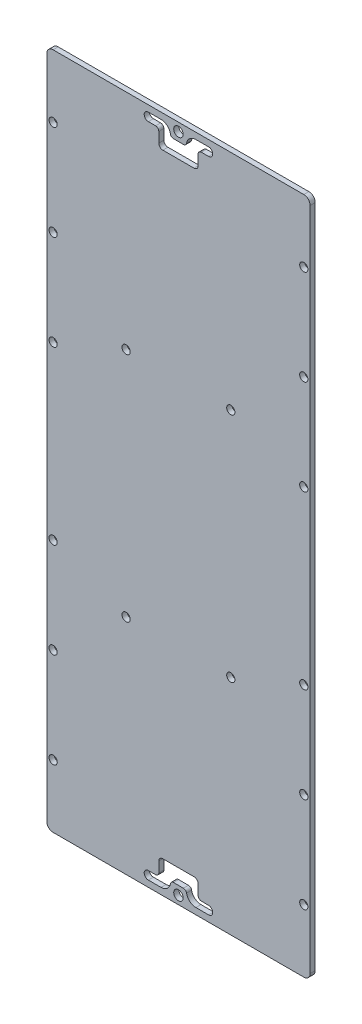
SolidWorks part; units mm, degrees
ref_plane "Front Plane" through (0, 0, 0) normal (0, 0, 1) x (1, 0, 0)
ref_plane "Top Plane" through (0, 0, 0) normal (0, 1, 0) x (1, 0, 0)
ref_plane "Right Plane" through (0, 0, 0) normal (1, 0, 0) x (0, 0, -1)
sketch "Model" plane through (0, 0, 0) normal (0, 0, 1) x (1, 0, 0)
  line L0 (28.681, 197.556) -> (29.189, 197.556) construction
  line L1 (29.189, 197.556) -> (29.189, 197.429) construction
  line L2 (29.189, 197.429) -> (28.681, 197.429) construction
  line L3 (28.681, 197.429) -> (28.681, 197.556) construction
  line L4 (28.681, 196.286) -> (29.189, 196.286) construction
  line L5 (29.189, 196.286) -> (29.189, 196.159) construction
  line L6 (29.189, 196.159) -> (28.681, 196.159) construction
  line L7 (28.681, 196.159) -> (28.681, 196.286) construction
  line L8 (52.811, 197.556) -> (53.319, 197.556) construction
  line L9 (53.319, 197.556) -> (53.319, 197.429) construction
  line L10 (53.319, 197.429) -> (52.811, 197.429) construction
  line L11 (52.811, 197.429) -> (52.811, 197.556) construction
  line L12 (52.811, 196.286) -> (53.319, 196.286) construction
  line L13 (53.319, 196.286) -> (53.319, 196.159) construction
  line L14 (53.319, 196.159) -> (52.811, 196.159) construction
  line L15 (52.811, 196.159) -> (52.811, 196.286) construction
  line L16 (29.189, 197.556) -> (28.681, 197.429) construction
  line L17 (29.189, 196.286) -> (28.681, 196.159) construction
  line L18 (53.319, 196.286) -> (52.811, 196.159) construction
  line L19 (53.319, 197.556) -> (52.811, 197.429) construction
  line L20 (53.065, 197.4925) -> (28.935, 196.2225) construction
  line L21 (28.935, 197.4925) -> (53.065, 196.2225) construction
  line L22 (29.189, 23.886) -> (52.811, 25.029)
  line L23 (53.319, 25.156) -> (52.811, 25.156)
  line L24 (53.319, 25.029) -> (53.319, 25.156)
  line L25 (52.811, 25.029) -> (53.319, 25.029)
  line L26 (52.811, 25.156) -> (52.811, 25.029)
  line L27 (29.189, 23.886) -> (28.681, 23.886)
  line L28 (29.189, 23.759) -> (29.189, 23.886)
  line L29 (28.681, 23.759) -> (29.189, 23.759)
  line L30 (28.681, 23.886) -> (28.681, 23.759)
  line L31 (29.189, 25.029) -> (52.811, 23.886)
  line L32 (53.319, 23.886) -> (52.811, 23.886)
  line L33 (53.319, 23.759) -> (53.319, 23.886)
  line L34 (52.811, 23.759) -> (53.319, 23.759)
  line L35 (52.811, 23.886) -> (52.811, 23.759)
  line L36 (29.189, 25.156) -> (28.681, 25.156)
  line L37 (29.189, 25.029) -> (29.189, 25.156)
  line L38 (28.681, 25.029) -> (29.189, 25.029)
  line L39 (28.681, 25.156) -> (28.681, 25.029)
  line L40 (8.0898, 14.859) -> (31.7118, 16.002)
  line L41 (32.2198, 16.129) -> (31.7118, 16.129)
  line L42 (32.2198, 16.002) -> (32.2198, 16.129)
  line L43 (31.7118, 16.002) -> (32.2198, 16.002)
  line L44 (31.7118, 16.129) -> (31.7118, 16.002)
  line L45 (8.0898, 14.859) -> (7.5818, 14.859)
  line L46 (8.0898, 14.732) -> (8.0898, 14.859)
  line L47 (7.5818, 14.732) -> (8.0898, 14.732)
  line L48 (7.5818, 14.859) -> (7.5818, 14.732)
  line L49 (8.0898, 16.002) -> (31.7118, 14.859)
  line L50 (32.2198, 14.859) -> (31.7118, 14.859)
  line L51 (32.2198, 14.732) -> (32.2198, 14.859)
  line L52 (31.7118, 14.732) -> (32.2198, 14.732)
  line L53 (31.7118, 14.859) -> (31.7118, 14.732)
  line L54 (8.0898, 16.129) -> (7.5818, 16.129)
  line L55 (8.0898, 16.002) -> (8.0898, 16.129)
  line L56 (7.5818, 16.002) -> (8.0898, 16.002)
  line L57 (7.5818, 16.129) -> (7.5818, 16.002)
  line L58 (7.5818, 207.6156) -> (8.0898, 207.6156)
  line L59 (8.0898, 207.6156) -> (8.0898, 207.4886)
  line L60 (8.0898, 207.4886) -> (7.5818, 207.4886)
  line L61 (7.5818, 207.4886) -> (7.5818, 207.6156)
  line L62 (7.5818, 206.3456) -> (8.0898, 206.3456)
  line L63 (8.0898, 206.3456) -> (8.0898, 206.2186)
  line L64 (8.0898, 206.2186) -> (7.5818, 206.2186)
  line L65 (7.5818, 206.2186) -> (7.5818, 206.3456)
  line L66 (31.7118, 207.6156) -> (32.2198, 207.6156)
  line L67 (32.2198, 207.6156) -> (32.2198, 207.4886)
  line L68 (32.2198, 207.4886) -> (31.7118, 207.4886)
  line L69 (31.7118, 207.4886) -> (31.7118, 207.6156)
  line L70 (31.7118, 206.3456) -> (32.2198, 206.3456)
  line L71 (32.2198, 206.3456) -> (32.2198, 206.2186)
  line L72 (32.2198, 206.2186) -> (31.7118, 206.2186)
  line L73 (31.7118, 206.2186) -> (31.7118, 206.3456)
  line L74 (8.0898, 207.6156) -> (7.5818, 207.4886)
  line L75 (8.0898, 206.3456) -> (7.5818, 206.2186)
  line L76 (-8.5, 204) -> (90.5, 204)
  line L77 (-8.5, 202.4) -> (90.5, 202.4)
  line L78 (-8.5, 11.6) -> (90.5, 11.6)
  line L79 (90.5, 11.6) -> (90.5, 10)
  line L80 (-8.5, 11.6) -> (-8.5, 10)
  line L81 (-8.5, 204) -> (-8.5, 202.4)
  line L82 (-8.5, 11.6) -> (-8.5, 10)
  line L83 (90.5, 11.6) -> (90.5, 10)
  line L84 (90.5, 204) -> (90.5, 202.4)
  line L85 (-8.5, 10) -> (90.5, 10)
  line L86 (29.189, 33.886) -> (52.811, 35.029)
  line L87 (53.319, 35.156) -> (52.811, 35.156)
  line L88 (53.319, 35.029) -> (53.319, 35.156)
  line L89 (52.811, 35.029) -> (53.319, 35.029)
  line L90 (52.811, 35.156) -> (52.811, 35.029)
  line L91 (29.189, 33.886) -> (28.681, 33.886)
  line L92 (29.189, 33.759) -> (29.189, 33.886)
  line L93 (28.681, 33.759) -> (29.189, 33.759)
  line L94 (28.681, 33.886) -> (28.681, 33.759)
  line L95 (29.189, 35.029) -> (52.811, 33.886)
  line L96 (53.319, 33.886) -> (52.811, 33.886)
  line L97 (53.319, 33.759) -> (53.319, 33.886)
  line L98 (52.811, 33.759) -> (53.319, 33.759)
  line L99 (52.811, 33.886) -> (52.811, 33.759)
  line L100 (29.189, 35.156) -> (28.681, 35.156)
  line L101 (29.189, 35.029) -> (29.189, 35.156)
  line L102 (28.681, 35.029) -> (29.189, 35.029)
  line L103 (28.681, 35.156) -> (28.681, 35.029)
  line L104 (29.189, 43.886) -> (52.811, 45.029)
  line L105 (53.319, 45.156) -> (52.811, 45.156)
  line L106 (53.319, 45.029) -> (53.319, 45.156)
  line L107 (52.811, 45.029) -> (53.319, 45.029)
  line L108 (52.811, 45.156) -> (52.811, 45.029)
  line L109 (29.189, 43.886) -> (28.681, 43.886)
  line L110 (29.189, 43.759) -> (29.189, 43.886)
  line L111 (28.681, 43.759) -> (29.189, 43.759)
  line L112 (28.681, 43.886) -> (28.681, 43.759)
  line L113 (29.189, 45.029) -> (52.811, 43.886)
  line L114 (53.319, 43.886) -> (52.811, 43.886)
  line L115 (53.319, 43.759) -> (53.319, 43.886)
  line L116 (52.811, 43.759) -> (53.319, 43.759)
  line L117 (52.811, 43.886) -> (52.811, 43.759)
  line L118 (29.189, 45.156) -> (28.681, 45.156)
  line L119 (29.189, 45.029) -> (29.189, 45.156)
  line L120 (28.681, 45.029) -> (29.189, 45.029)
  line L121 (28.681, 45.156) -> (28.681, 45.029)
  line L122 (29.189, 53.886) -> (52.811, 55.029)
  line L123 (53.319, 55.156) -> (52.811, 55.156)
  line L124 (53.319, 55.029) -> (53.319, 55.156)
  line L125 (52.811, 55.029) -> (53.319, 55.029)
  line L126 (52.811, 55.156) -> (52.811, 55.029)
  line L127 (29.189, 53.886) -> (28.681, 53.886)
  line L128 (29.189, 53.759) -> (29.189, 53.886)
  line L129 (28.681, 53.759) -> (29.189, 53.759)
  line L130 (28.681, 53.886) -> (28.681, 53.759)
  line L131 (29.189, 55.029) -> (52.811, 53.886)
  line L132 (53.319, 53.886) -> (52.811, 53.886)
  line L133 (53.319, 53.759) -> (53.319, 53.886)
  line L134 (52.811, 53.759) -> (53.319, 53.759)
  line L135 (52.811, 53.886) -> (52.811, 53.759)
  line L136 (29.189, 55.156) -> (28.681, 55.156)
  line L137 (29.189, 55.029) -> (29.189, 55.156)
  line L138 (28.681, 55.029) -> (29.189, 55.029)
  line L139 (28.681, 55.156) -> (28.681, 55.029)
  line L140 (29.189, 63.886) -> (52.811, 65.029)
  line L141 (53.319, 65.156) -> (52.811, 65.156)
  line L142 (53.319, 65.029) -> (53.319, 65.156)
  line L143 (52.811, 65.029) -> (53.319, 65.029)
  line L144 (52.811, 65.156) -> (52.811, 65.029)
  line L145 (29.189, 63.886) -> (28.681, 63.886)
  line L146 (29.189, 63.759) -> (29.189, 63.886)
  line L147 (28.681, 63.759) -> (29.189, 63.759)
  line L148 (28.681, 63.886) -> (28.681, 63.759)
  line L149 (29.189, 65.029) -> (52.811, 63.886)
  line L150 (53.319, 63.886) -> (52.811, 63.886)
  line L151 (53.319, 63.759) -> (53.319, 63.886)
  line L152 (52.811, 63.759) -> (53.319, 63.759)
  line L153 (52.811, 63.886) -> (52.811, 63.759)
  line L154 (29.189, 65.156) -> (28.681, 65.156)
  line L155 (29.189, 65.029) -> (29.189, 65.156)
  line L156 (28.681, 65.029) -> (29.189, 65.029)
  line L157 (28.681, 65.156) -> (28.681, 65.029)
  line L158 (29.189, 73.886) -> (52.811, 75.029)
  line L159 (53.319, 75.156) -> (52.811, 75.156)
  line L160 (53.319, 75.029) -> (53.319, 75.156)
  line L161 (52.811, 75.029) -> (53.319, 75.029)
  line L162 (52.811, 75.156) -> (52.811, 75.029)
  line L163 (29.189, 73.886) -> (28.681, 73.886)
  line L164 (29.189, 73.759) -> (29.189, 73.886)
  line L165 (28.681, 73.759) -> (29.189, 73.759)
  line L166 (28.681, 73.886) -> (28.681, 73.759)
  line L167 (29.189, 75.029) -> (52.811, 73.886)
  line L168 (53.319, 73.886) -> (52.811, 73.886)
  line L169 (53.319, 73.759) -> (53.319, 73.886)
  line L170 (52.811, 73.759) -> (53.319, 73.759)
  line L171 (52.811, 73.886) -> (52.811, 73.759)
  line L172 (29.189, 75.156) -> (28.681, 75.156)
  line L173 (29.189, 75.029) -> (29.189, 75.156)
  line L174 (28.681, 75.029) -> (29.189, 75.029)
  line L175 (28.681, 75.156) -> (28.681, 75.029)
  line L176 (29.189, 83.886) -> (52.811, 85.029)
  line L177 (53.319, 85.156) -> (52.811, 85.156)
  line L178 (53.319, 85.029) -> (53.319, 85.156)
  line L179 (52.811, 85.029) -> (53.319, 85.029)
  line L180 (52.811, 85.156) -> (52.811, 85.029)
  line L181 (29.189, 83.886) -> (28.681, 83.886)
  line L182 (29.189, 83.759) -> (29.189, 83.886)
  line L183 (28.681, 83.759) -> (29.189, 83.759)
  line L184 (28.681, 83.886) -> (28.681, 83.759)
  line L185 (29.189, 85.029) -> (52.811, 83.886)
  line L186 (53.319, 83.886) -> (52.811, 83.886)
  line L187 (53.319, 83.759) -> (53.319, 83.886)
  line L188 (52.811, 83.759) -> (53.319, 83.759)
  line L189 (52.811, 83.886) -> (52.811, 83.759)
  line L190 (29.189, 85.156) -> (28.681, 85.156)
  line L191 (29.189, 85.029) -> (29.189, 85.156)
  line L192 (28.681, 85.029) -> (29.189, 85.029)
  line L193 (28.681, 85.156) -> (28.681, 85.029)
  line L194 (29.189, 93.886) -> (52.811, 95.029)
  line L195 (53.319, 95.156) -> (52.811, 95.156)
  line L196 (53.319, 95.029) -> (53.319, 95.156)
  line L197 (52.811, 95.029) -> (53.319, 95.029)
  line L198 (52.811, 95.156) -> (52.811, 95.029)
  line L199 (29.189, 93.886) -> (28.681, 93.886)
  line L200 (29.189, 93.759) -> (29.189, 93.886)
  line L201 (28.681, 93.759) -> (29.189, 93.759)
  line L202 (28.681, 93.886) -> (28.681, 93.759)
  line L203 (29.189, 95.029) -> (52.811, 93.886)
  line L204 (53.319, 93.886) -> (52.811, 93.886)
  line L205 (53.319, 93.759) -> (53.319, 93.886)
  line L206 (52.811, 93.759) -> (53.319, 93.759)
  line L207 (52.811, 93.886) -> (52.811, 93.759)
  line L208 (29.189, 95.156) -> (28.681, 95.156)
  line L209 (29.189, 95.029) -> (29.189, 95.156)
  line L210 (28.681, 95.029) -> (29.189, 95.029)
  line L211 (28.681, 95.156) -> (28.681, 95.029)
  line L212 (29.189, 103.886) -> (52.811, 105.029)
  line L213 (53.319, 105.156) -> (52.811, 105.156)
  line L214 (53.319, 105.029) -> (53.319, 105.156)
  line L215 (52.811, 105.029) -> (53.319, 105.029)
  line L216 (52.811, 105.156) -> (52.811, 105.029)
  line L217 (29.189, 103.886) -> (28.681, 103.886)
  line L218 (29.189, 103.759) -> (29.189, 103.886)
  line L219 (28.681, 103.759) -> (29.189, 103.759)
  line L220 (28.681, 103.886) -> (28.681, 103.759)
  line L221 (29.189, 105.029) -> (52.811, 103.886)
  line L222 (53.319, 103.886) -> (52.811, 103.886)
  line L223 (53.319, 103.759) -> (53.319, 103.886)
  line L224 (52.811, 103.759) -> (53.319, 103.759)
  line L225 (52.811, 103.886) -> (52.811, 103.759)
  line L226 (29.189, 105.156) -> (28.681, 105.156)
  line L227 (29.189, 105.029) -> (29.189, 105.156)
  line L228 (28.681, 105.029) -> (29.189, 105.029)
  line L229 (28.681, 105.156) -> (28.681, 105.029)
  line L230 (19.4182, 23.886) -> (19.0118, 23.886)
  line L231 (19.4182, 23.759) -> (19.4182, 23.886)
  line L232 (19.0118, 23.759) -> (19.4182, 23.759)
  line L233 (19.0118, 23.886) -> (19.0118, 23.759)
  line L234 (19.4182, 25.156) -> (19.0118, 25.156)
  line L235 (19.4182, 25.029) -> (19.4182, 25.156)
  line L236 (19.0118, 25.029) -> (19.4182, 25.029)
  line L237 (19.0118, 25.156) -> (19.0118, 25.029)
  line L238 (7.9882, 25.156) -> (7.5818, 25.156)
  line L239 (7.9882, 25.029) -> (7.9882, 25.156)
  line L240 (7.5818, 25.029) -> (7.9882, 25.029)
  line L241 (7.5818, 25.156) -> (7.5818, 25.029)
  line L242 (7.9882, 23.886) -> (7.5818, 23.886)
  line L243 (7.9882, 23.759) -> (7.9882, 23.886)
  line L244 (7.5818, 23.759) -> (7.9882, 23.759)
  line L245 (7.5818, 23.886) -> (7.5818, 23.759)
  line L246 (-8.5, 21.6) -> (90.5, 21.6)
  line L247 (90.5, 21.6) -> (90.5, 20)
  line L248 (-8.5, 21.6) -> (-8.5, 20)
  line L249 (-8.5, 21.6) -> (-8.5, 20)
  line L250 (90.5, 21.6) -> (90.5, 20)
  line L251 (-8.5, 20) -> (90.5, 20)
  line L252 (7.9882, 25.156) -> (19.0118, 23.759) construction
  line L253 (19.0118, 25.156) -> (7.9882, 23.759) construction
  line L254 (19.4182, 33.886) -> (19.0118, 33.886)
  line L255 (19.4182, 33.759) -> (19.4182, 33.886)
  line L256 (19.0118, 33.759) -> (19.4182, 33.759)
  line L257 (19.0118, 33.886) -> (19.0118, 33.759)
  line L258 (19.4182, 35.156) -> (19.0118, 35.156)
  line L259 (19.4182, 35.029) -> (19.4182, 35.156)
  line L260 (19.0118, 35.029) -> (19.4182, 35.029)
  line L261 (19.0118, 35.156) -> (19.0118, 35.029)
  line L262 (7.9882, 35.156) -> (7.5818, 35.156)
  line L263 (7.9882, 35.029) -> (7.9882, 35.156)
  line L264 (7.5818, 35.029) -> (7.9882, 35.029)
  line L265 (7.5818, 35.156) -> (7.5818, 35.029)
  line L266 (7.9882, 33.886) -> (7.5818, 33.886)
  line L267 (7.9882, 33.759) -> (7.9882, 33.886)
  line L268 (7.5818, 33.759) -> (7.9882, 33.759)
  line L269 (7.5818, 33.886) -> (7.5818, 33.759)
  line L270 (-8.5, 31.6) -> (90.5, 31.6)
  line L271 (90.5, 31.6) -> (90.5, 30)
  line L272 (-8.5, 31.6) -> (-8.5, 30)
  line L273 (-8.5, 31.6) -> (-8.5, 30)
  line L274 (90.5, 31.6) -> (90.5, 30)
  line L275 (-8.5, 30) -> (90.5, 30)
  line L276 (7.9882, 35.156) -> (19.0118, 33.759) construction
  line L277 (19.0118, 35.156) -> (7.9882, 33.759) construction
  line L278 (19.4182, 43.886) -> (19.0118, 43.886)
  line L279 (19.4182, 43.759) -> (19.4182, 43.886)
  line L280 (19.0118, 43.759) -> (19.4182, 43.759)
  line L281 (19.0118, 43.886) -> (19.0118, 43.759)
  line L282 (19.4182, 45.156) -> (19.0118, 45.156)
  line L283 (19.4182, 45.029) -> (19.4182, 45.156)
  line L284 (19.0118, 45.029) -> (19.4182, 45.029)
  line L285 (19.0118, 45.156) -> (19.0118, 45.029)
  line L286 (7.9882, 45.156) -> (7.5818, 45.156)
  line L287 (7.9882, 45.029) -> (7.9882, 45.156)
  line L288 (7.5818, 45.029) -> (7.9882, 45.029)
  line L289 (7.5818, 45.156) -> (7.5818, 45.029)
  line L290 (7.9882, 43.886) -> (7.5818, 43.886)
  line L291 (7.9882, 43.759) -> (7.9882, 43.886)
  line L292 (7.5818, 43.759) -> (7.9882, 43.759)
  line L293 (7.5818, 43.886) -> (7.5818, 43.759)
  line L294 (-8.5, 41.6) -> (90.5, 41.6)
  line L295 (90.5, 41.6) -> (90.5, 40)
  line L296 (-8.5, 41.6) -> (-8.5, 40)
  line L297 (-8.5, 41.6) -> (-8.5, 40)
  line L298 (90.5, 41.6) -> (90.5, 40)
  line L299 (-8.5, 40) -> (90.5, 40)
  line L300 (7.9882, 45.156) -> (19.0118, 43.759) construction
  line L301 (19.0118, 45.156) -> (7.9882, 43.759) construction
  line L302 (19.4182, 53.886) -> (19.0118, 53.886)
  line L303 (19.4182, 53.759) -> (19.4182, 53.886)
  line L304 (19.0118, 53.759) -> (19.4182, 53.759)
  line L305 (19.0118, 53.886) -> (19.0118, 53.759)
  line L306 (19.4182, 55.156) -> (19.0118, 55.156)
  line L307 (19.4182, 55.029) -> (19.4182, 55.156)
  line L308 (19.0118, 55.029) -> (19.4182, 55.029)
  line L309 (19.0118, 55.156) -> (19.0118, 55.029)
  line L310 (7.9882, 55.156) -> (7.5818, 55.156)
  line L311 (7.9882, 55.029) -> (7.9882, 55.156)
  line L312 (7.5818, 55.029) -> (7.9882, 55.029)
  line L313 (7.5818, 55.156) -> (7.5818, 55.029)
  line L314 (7.9882, 53.886) -> (7.5818, 53.886)
  line L315 (7.9882, 53.759) -> (7.9882, 53.886)
  line L316 (7.5818, 53.759) -> (7.9882, 53.759)
  line L317 (7.5818, 53.886) -> (7.5818, 53.759)
  line L318 (-8.5, 51.6) -> (90.5, 51.6)
  line L319 (90.5, 51.6) -> (90.5, 50)
  line L320 (-8.5, 51.6) -> (-8.5, 50)
  line L321 (-8.5, 51.6) -> (-8.5, 50)
  line L322 (90.5, 51.6) -> (90.5, 50)
  line L323 (-8.5, 50) -> (90.5, 50)
  line L324 (7.9882, 55.156) -> (19.0118, 53.759) construction
  line L325 (19.0118, 55.156) -> (7.9882, 53.759) construction
  line L326 (19.4182, 63.886) -> (19.0118, 63.886)
  line L327 (19.4182, 63.759) -> (19.4182, 63.886)
  line L328 (19.0118, 63.759) -> (19.4182, 63.759)
  line L329 (19.0118, 63.886) -> (19.0118, 63.759)
  line L330 (19.4182, 65.156) -> (19.0118, 65.156)
  line L331 (19.4182, 65.029) -> (19.4182, 65.156)
  line L332 (19.0118, 65.029) -> (19.4182, 65.029)
  line L333 (19.0118, 65.156) -> (19.0118, 65.029)
  line L334 (7.9882, 65.156) -> (7.5818, 65.156)
  line L335 (7.9882, 65.029) -> (7.9882, 65.156)
  line L336 (7.5818, 65.029) -> (7.9882, 65.029)
  line L337 (7.5818, 65.156) -> (7.5818, 65.029)
  line L338 (7.9882, 63.886) -> (7.5818, 63.886)
  line L339 (7.9882, 63.759) -> (7.9882, 63.886)
  line L340 (7.5818, 63.759) -> (7.9882, 63.759)
  line L341 (7.5818, 63.886) -> (7.5818, 63.759)
  line L342 (-8.5, 61.6) -> (90.5, 61.6)
  line L343 (90.5, 61.6) -> (90.5, 60)
  line L344 (-8.5, 61.6) -> (-8.5, 60)
  line L345 (-8.5, 61.6) -> (-8.5, 60)
  line L346 (90.5, 61.6) -> (90.5, 60)
  line L347 (-8.5, 60) -> (90.5, 60)
  line L348 (7.9882, 65.156) -> (19.0118, 63.759) construction
  line L349 (19.0118, 65.156) -> (7.9882, 63.759) construction
  line L350 (19.4182, 73.886) -> (19.0118, 73.886)
  line L351 (19.4182, 73.759) -> (19.4182, 73.886)
  line L352 (19.0118, 73.759) -> (19.4182, 73.759)
  line L353 (19.0118, 73.886) -> (19.0118, 73.759)
  line L354 (19.4182, 75.156) -> (19.0118, 75.156)
  line L355 (19.4182, 75.029) -> (19.4182, 75.156)
  line L356 (19.0118, 75.029) -> (19.4182, 75.029)
  line L357 (19.0118, 75.156) -> (19.0118, 75.029)
  line L358 (7.9882, 75.156) -> (7.5818, 75.156)
  line L359 (7.9882, 75.029) -> (7.9882, 75.156)
  line L360 (7.5818, 75.029) -> (7.9882, 75.029)
  line L361 (7.5818, 75.156) -> (7.5818, 75.029)
  line L362 (7.9882, 73.886) -> (7.5818, 73.886)
  line L363 (7.9882, 73.759) -> (7.9882, 73.886)
  line L364 (7.5818, 73.759) -> (7.9882, 73.759)
  line L365 (7.5818, 73.886) -> (7.5818, 73.759)
  line L366 (-8.5, 71.6) -> (90.5, 71.6)
  line L367 (90.5, 71.6) -> (90.5, 70)
  line L368 (-8.5, 71.6) -> (-8.5, 70)
  line L369 (-8.5, 71.6) -> (-8.5, 70)
  line L370 (90.5, 71.6) -> (90.5, 70)
  line L371 (-8.5, 70) -> (90.5, 70)
  line L372 (7.9882, 75.156) -> (19.0118, 73.759) construction
  line L373 (19.0118, 75.156) -> (7.9882, 73.759) construction
  line L374 (19.4182, 83.886) -> (19.0118, 83.886)
  line L375 (19.4182, 83.759) -> (19.4182, 83.886)
  line L376 (19.0118, 83.759) -> (19.4182, 83.759)
  line L377 (19.0118, 83.886) -> (19.0118, 83.759)
  line L378 (19.4182, 85.156) -> (19.0118, 85.156)
  line L379 (19.4182, 85.029) -> (19.4182, 85.156)
  line L380 (19.0118, 85.029) -> (19.4182, 85.029)
  line L381 (19.0118, 85.156) -> (19.0118, 85.029)
  line L382 (7.9882, 85.156) -> (7.5818, 85.156)
  line L383 (7.9882, 85.029) -> (7.9882, 85.156)
  line L384 (7.5818, 85.029) -> (7.9882, 85.029)
  line L385 (7.5818, 85.156) -> (7.5818, 85.029)
  line L386 (7.9882, 83.886) -> (7.5818, 83.886)
  line L387 (7.9882, 83.759) -> (7.9882, 83.886)
  line L388 (7.5818, 83.759) -> (7.9882, 83.759)
  line L389 (7.5818, 83.886) -> (7.5818, 83.759)
  line L390 (-8.5, 81.6) -> (90.5, 81.6)
  line L391 (90.5, 81.6) -> (90.5, 80)
  line L392 (-8.5, 81.6) -> (-8.5, 80)
  line L393 (-8.5, 81.6) -> (-8.5, 80)
  line L394 (90.5, 81.6) -> (90.5, 80)
  line L395 (-8.5, 80) -> (90.5, 80)
  line L396 (7.9882, 85.156) -> (19.0118, 83.759) construction
  line L397 (19.0118, 85.156) -> (7.9882, 83.759) construction
  line L398 (19.4182, 93.886) -> (19.0118, 93.886)
  line L399 (19.4182, 93.759) -> (19.4182, 93.886)
  line L400 (19.0118, 93.759) -> (19.4182, 93.759)
  line L401 (19.0118, 93.886) -> (19.0118, 93.759)
  line L402 (19.4182, 95.156) -> (19.0118, 95.156)
  line L403 (19.4182, 95.029) -> (19.4182, 95.156)
  line L404 (19.0118, 95.029) -> (19.4182, 95.029)
  line L405 (19.0118, 95.156) -> (19.0118, 95.029)
  line L406 (7.9882, 95.156) -> (7.5818, 95.156)
  line L407 (7.9882, 95.029) -> (7.9882, 95.156)
  line L408 (7.5818, 95.029) -> (7.9882, 95.029)
  line L409 (7.5818, 95.156) -> (7.5818, 95.029)
  line L410 (7.9882, 93.886) -> (7.5818, 93.886)
  line L411 (7.9882, 93.759) -> (7.9882, 93.886)
  line L412 (7.5818, 93.759) -> (7.9882, 93.759)
  line L413 (7.5818, 93.886) -> (7.5818, 93.759)
  line L414 (-8.5, 91.6) -> (90.5, 91.6)
  line L415 (90.5, 91.6) -> (90.5, 90)
  line L416 (-8.5, 91.6) -> (-8.5, 90)
  line L417 (-8.5, 91.6) -> (-8.5, 90)
  line L418 (90.5, 91.6) -> (90.5, 90)
  line L419 (-8.5, 90) -> (90.5, 90)
  line L420 (7.9882, 95.156) -> (19.0118, 93.759) construction
  line L421 (19.0118, 95.156) -> (7.9882, 93.759) construction
  line L422 (19.4182, 103.886) -> (19.0118, 103.886)
  line L423 (19.4182, 103.759) -> (19.4182, 103.886)
  line L424 (19.0118, 103.759) -> (19.4182, 103.759)
  line L425 (19.0118, 103.886) -> (19.0118, 103.759)
  line L426 (19.4182, 105.156) -> (19.0118, 105.156)
  line L427 (19.4182, 105.029) -> (19.4182, 105.156)
  line L428 (19.0118, 105.029) -> (19.4182, 105.029)
  line L429 (19.0118, 105.156) -> (19.0118, 105.029)
  line L430 (7.9882, 105.156) -> (7.5818, 105.156)
  line L431 (7.9882, 105.029) -> (7.9882, 105.156)
  line L432 (7.5818, 105.029) -> (7.9882, 105.029)
  line L433 (7.5818, 105.156) -> (7.5818, 105.029)
  line L434 (7.9882, 103.886) -> (7.5818, 103.886)
  line L435 (7.9882, 103.759) -> (7.9882, 103.886)
  line L436 (7.5818, 103.759) -> (7.9882, 103.759)
  line L437 (7.5818, 103.886) -> (7.5818, 103.759)
  line L438 (-8.5, 101.6) -> (90.5, 101.6)
  line L439 (90.5, 101.6) -> (90.5, 100)
  line L440 (-8.5, 101.6) -> (-8.5, 100)
  line L441 (-8.5, 101.6) -> (-8.5, 100)
  line L442 (90.5, 101.6) -> (90.5, 100)
  line L443 (-8.5, 100) -> (90.5, 100)
  line L444 (7.9882, 105.156) -> (19.0118, 103.759) construction
  line L445 (19.0118, 105.156) -> (7.9882, 103.759) construction
  line L446 (28.681, 187.556) -> (29.189, 187.556) construction
  line L447 (29.189, 187.556) -> (29.189, 187.429) construction
  line L448 (29.189, 187.429) -> (28.681, 187.429) construction
  line L449 (28.681, 187.429) -> (28.681, 187.556) construction
  line L450 (28.681, 186.286) -> (29.189, 186.286) construction
  line L451 (29.189, 186.286) -> (29.189, 186.159) construction
  line L452 (29.189, 186.159) -> (28.681, 186.159) construction
  line L453 (28.681, 186.159) -> (28.681, 186.286) construction
  line L454 (52.811, 187.556) -> (53.319, 187.556) construction
  line L455 (53.319, 187.556) -> (53.319, 187.429) construction
  line L456 (53.319, 187.429) -> (52.811, 187.429) construction
  line L457 (52.811, 187.429) -> (52.811, 187.556) construction
  line L458 (52.811, 186.286) -> (53.319, 186.286) construction
  line L459 (53.319, 186.286) -> (53.319, 186.159) construction
  line L460 (53.319, 186.159) -> (52.811, 186.159) construction
  line L461 (52.811, 186.159) -> (52.811, 186.286) construction
  line L462 (29.189, 187.556) -> (28.681, 187.429) construction
  line L463 (29.189, 186.286) -> (28.681, 186.159) construction
  line L464 (53.319, 186.286) -> (52.811, 186.159) construction
  line L465 (53.319, 187.556) -> (52.811, 187.429) construction
  line L466 (53.065, 187.4925) -> (28.935, 186.2225) construction
  line L467 (28.935, 187.4925) -> (53.065, 186.2225) construction
  line L468 (28.681, 177.556) -> (29.189, 177.556) construction
  line L469 (29.189, 177.556) -> (29.189, 177.429) construction
  line L470 (29.189, 177.429) -> (28.681, 177.429) construction
  line L471 (28.681, 177.429) -> (28.681, 177.556) construction
  line L472 (28.681, 176.286) -> (29.189, 176.286) construction
  line L473 (29.189, 176.286) -> (29.189, 176.159) construction
  line L474 (29.189, 176.159) -> (28.681, 176.159) construction
  line L475 (28.681, 176.159) -> (28.681, 176.286) construction
  line L476 (52.811, 177.556) -> (53.319, 177.556) construction
  line L477 (53.319, 177.556) -> (53.319, 177.429) construction
  line L478 (53.319, 177.429) -> (52.811, 177.429) construction
  line L479 (52.811, 177.429) -> (52.811, 177.556) construction
  line L480 (52.811, 176.286) -> (53.319, 176.286) construction
  line L481 (53.319, 176.286) -> (53.319, 176.159) construction
  line L482 (53.319, 176.159) -> (52.811, 176.159) construction
  line L483 (52.811, 176.159) -> (52.811, 176.286) construction
  line L484 (29.189, 177.556) -> (28.681, 177.429) construction
  line L485 (29.189, 176.286) -> (28.681, 176.159) construction
  line L486 (53.319, 176.286) -> (52.811, 176.159) construction
  line L487 (53.319, 177.556) -> (52.811, 177.429) construction
  line L488 (53.065, 177.4925) -> (28.935, 176.2225) construction
  line L489 (28.935, 177.4925) -> (53.065, 176.2225) construction
  line L490 (28.681, 167.556) -> (29.189, 167.556) construction
  line L491 (29.189, 167.556) -> (29.189, 167.429) construction
  line L492 (29.189, 167.429) -> (28.681, 167.429) construction
  line L493 (28.681, 167.429) -> (28.681, 167.556) construction
  line L494 (28.681, 166.286) -> (29.189, 166.286) construction
  line L495 (29.189, 166.286) -> (29.189, 166.159) construction
  line L496 (29.189, 166.159) -> (28.681, 166.159) construction
  line L497 (28.681, 166.159) -> (28.681, 166.286) construction
  line L498 (52.811, 167.556) -> (53.319, 167.556) construction
  line L499 (53.319, 167.556) -> (53.319, 167.429) construction
  line L500 (53.319, 167.429) -> (52.811, 167.429) construction
  line L501 (52.811, 167.429) -> (52.811, 167.556) construction
  line L502 (52.811, 166.286) -> (53.319, 166.286) construction
  line L503 (53.319, 166.286) -> (53.319, 166.159) construction
  line L504 (53.319, 166.159) -> (52.811, 166.159) construction
  line L505 (52.811, 166.159) -> (52.811, 166.286) construction
  line L506 (29.189, 167.556) -> (28.681, 167.429) construction
  line L507 (29.189, 166.286) -> (28.681, 166.159) construction
  line L508 (53.319, 166.286) -> (52.811, 166.159) construction
  line L509 (53.319, 167.556) -> (52.811, 167.429) construction
  line L510 (53.065, 167.4925) -> (28.935, 166.2225) construction
  line L511 (28.935, 167.4925) -> (53.065, 166.2225) construction
  line L512 (28.681, 157.556) -> (29.189, 157.556) construction
  line L513 (29.189, 157.556) -> (29.189, 157.429) construction
  line L514 (29.189, 157.429) -> (28.681, 157.429) construction
  line L515 (28.681, 157.429) -> (28.681, 157.556) construction
  line L516 (28.681, 156.286) -> (29.189, 156.286) construction
  line L517 (29.189, 156.286) -> (29.189, 156.159) construction
  line L518 (29.189, 156.159) -> (28.681, 156.159) construction
  line L519 (28.681, 156.159) -> (28.681, 156.286) construction
  line L520 (52.811, 157.556) -> (53.319, 157.556) construction
  line L521 (53.319, 157.556) -> (53.319, 157.429) construction
  line L522 (53.319, 157.429) -> (52.811, 157.429) construction
  line L523 (52.811, 157.429) -> (52.811, 157.556) construction
  line L524 (52.811, 156.286) -> (53.319, 156.286) construction
  line L525 (53.319, 156.286) -> (53.319, 156.159) construction
  line L526 (53.319, 156.159) -> (52.811, 156.159) construction
  line L527 (52.811, 156.159) -> (52.811, 156.286) construction
  line L528 (29.189, 157.556) -> (28.681, 157.429) construction
  line L529 (29.189, 156.286) -> (28.681, 156.159) construction
  line L530 (53.319, 156.286) -> (52.811, 156.159) construction
  line L531 (53.319, 157.556) -> (52.811, 157.429) construction
  line L532 (53.065, 157.4925) -> (28.935, 156.2225) construction
  line L533 (28.935, 157.4925) -> (53.065, 156.2225) construction
  line L534 (28.681, 147.556) -> (29.189, 147.556) construction
  line L535 (29.189, 147.556) -> (29.189, 147.429) construction
  line L536 (29.189, 147.429) -> (28.681, 147.429) construction
  line L537 (28.681, 147.429) -> (28.681, 147.556) construction
  line L538 (28.681, 146.286) -> (29.189, 146.286) construction
  line L539 (29.189, 146.286) -> (29.189, 146.159) construction
  line L540 (29.189, 146.159) -> (28.681, 146.159) construction
  line L541 (28.681, 146.159) -> (28.681, 146.286) construction
  line L542 (52.811, 147.556) -> (53.319, 147.556) construction
  line L543 (53.319, 147.556) -> (53.319, 147.429) construction
  line L544 (53.319, 147.429) -> (52.811, 147.429) construction
  line L545 (52.811, 147.429) -> (52.811, 147.556) construction
  line L546 (52.811, 146.286) -> (53.319, 146.286) construction
  line L547 (53.319, 146.286) -> (53.319, 146.159) construction
  line L548 (53.319, 146.159) -> (52.811, 146.159) construction
  line L549 (52.811, 146.159) -> (52.811, 146.286) construction
  line L550 (29.189, 147.556) -> (28.681, 147.429) construction
  line L551 (29.189, 146.286) -> (28.681, 146.159) construction
  line L552 (53.319, 146.286) -> (52.811, 146.159) construction
  line L553 (53.319, 147.556) -> (52.811, 147.429) construction
  line L554 (53.065, 147.4925) -> (28.935, 146.2225) construction
  line L555 (28.935, 147.4925) -> (53.065, 146.2225) construction
  line L556 (28.681, 137.556) -> (29.189, 137.556) construction
  line L557 (29.189, 137.556) -> (29.189, 137.429) construction
  line L558 (29.189, 137.429) -> (28.681, 137.429) construction
  line L559 (28.681, 137.429) -> (28.681, 137.556) construction
  line L560 (28.681, 136.286) -> (29.189, 136.286) construction
  line L561 (29.189, 136.286) -> (29.189, 136.159) construction
  line L562 (29.189, 136.159) -> (28.681, 136.159) construction
  line L563 (28.681, 136.159) -> (28.681, 136.286) construction
  line L564 (52.811, 137.556) -> (53.319, 137.556) construction
  line L565 (53.319, 137.556) -> (53.319, 137.429) construction
  line L566 (53.319, 137.429) -> (52.811, 137.429) construction
  line L567 (52.811, 137.429) -> (52.811, 137.556) construction
  line L568 (52.811, 136.286) -> (53.319, 136.286) construction
  line L569 (53.319, 136.286) -> (53.319, 136.159) construction
  line L570 (53.319, 136.159) -> (52.811, 136.159) construction
  line L571 (52.811, 136.159) -> (52.811, 136.286) construction
  line L572 (29.189, 137.556) -> (28.681, 137.429) construction
  line L573 (29.189, 136.286) -> (28.681, 136.159) construction
  line L574 (53.319, 136.286) -> (52.811, 136.159) construction
  line L575 (53.319, 137.556) -> (52.811, 137.429) construction
  line L576 (53.065, 137.4925) -> (28.935, 136.2225) construction
  line L577 (28.935, 137.4925) -> (53.065, 136.2225) construction
  line L578 (28.681, 127.556) -> (29.189, 127.556) construction
  line L579 (29.189, 127.556) -> (29.189, 127.429) construction
  line L580 (29.189, 127.429) -> (28.681, 127.429) construction
  line L581 (28.681, 127.429) -> (28.681, 127.556) construction
  line L582 (28.681, 126.286) -> (29.189, 126.286) construction
  line L583 (29.189, 126.286) -> (29.189, 126.159) construction
  line L584 (29.189, 126.159) -> (28.681, 126.159) construction
  line L585 (28.681, 126.159) -> (28.681, 126.286) construction
  line L586 (52.811, 127.556) -> (53.319, 127.556) construction
  line L587 (53.319, 127.556) -> (53.319, 127.429) construction
  line L588 (53.319, 127.429) -> (52.811, 127.429) construction
  line L589 (52.811, 127.429) -> (52.811, 127.556) construction
  line L590 (52.811, 126.286) -> (53.319, 126.286) construction
  line L591 (53.319, 126.286) -> (53.319, 126.159) construction
  line L592 (53.319, 126.159) -> (52.811, 126.159) construction
  line L593 (52.811, 126.159) -> (52.811, 126.286) construction
  line L594 (29.189, 127.556) -> (28.681, 127.429) construction
  line L595 (29.189, 126.286) -> (28.681, 126.159) construction
  line L596 (53.319, 126.286) -> (52.811, 126.159) construction
  line L597 (53.319, 127.556) -> (52.811, 127.429) construction
  line L598 (53.065, 127.4925) -> (28.935, 126.2225) construction
  line L599 (28.935, 127.4925) -> (53.065, 126.2225) construction
  line L600 (28.681, 117.556) -> (29.189, 117.556) construction
  line L601 (29.189, 117.556) -> (29.189, 117.429) construction
  line L602 (29.189, 117.429) -> (28.681, 117.429) construction
  line L603 (28.681, 117.429) -> (28.681, 117.556) construction
  line L604 (28.681, 116.286) -> (29.189, 116.286) construction
  line L605 (29.189, 116.286) -> (29.189, 116.159) construction
  line L606 (29.189, 116.159) -> (28.681, 116.159) construction
  line L607 (28.681, 116.159) -> (28.681, 116.286) construction
  line L608 (52.811, 117.556) -> (53.319, 117.556) construction
  line L609 (53.319, 117.556) -> (53.319, 117.429) construction
  line L610 (53.319, 117.429) -> (52.811, 117.429) construction
  line L611 (52.811, 117.429) -> (52.811, 117.556) construction
  line L612 (52.811, 116.286) -> (53.319, 116.286) construction
  line L613 (53.319, 116.286) -> (53.319, 116.159) construction
  line L614 (53.319, 116.159) -> (52.811, 116.159) construction
  line L615 (52.811, 116.159) -> (52.811, 116.286) construction
  line L616 (29.189, 117.556) -> (28.681, 117.429) construction
  line L617 (29.189, 116.286) -> (28.681, 116.159) construction
  line L618 (53.319, 116.286) -> (52.811, 116.159) construction
  line L619 (53.319, 117.556) -> (52.811, 117.429) construction
  line L620 (53.065, 117.4925) -> (28.935, 116.2225) construction
  line L621 (28.935, 117.4925) -> (53.065, 116.2225) construction
  line L622 (7.5818, 197.556) -> (7.9882, 197.556)
  line L623 (7.9882, 197.556) -> (7.9882, 197.429)
  line L624 (7.9882, 197.429) -> (7.5818, 197.429)
  line L625 (7.5818, 197.429) -> (7.5818, 197.556)
  line L626 (7.5818, 196.286) -> (7.9882, 196.286)
  line L627 (7.9882, 196.286) -> (7.9882, 196.159)
  line L628 (7.9882, 196.159) -> (7.5818, 196.159)
  line L629 (7.5818, 196.159) -> (7.5818, 196.286)
  line L630 (19.0118, 197.556) -> (19.4182, 197.556)
  line L631 (19.4182, 197.556) -> (19.4182, 197.429)
  line L632 (19.4182, 197.429) -> (19.0118, 197.429)
  line L633 (19.0118, 197.429) -> (19.0118, 197.556)
  line L634 (19.0118, 196.286) -> (19.4182, 196.286)
  line L635 (19.4182, 196.286) -> (19.4182, 196.159)
  line L636 (19.4182, 196.159) -> (19.0118, 196.159)
  line L637 (19.0118, 196.159) -> (19.0118, 196.286)
  line L638 (-8.5, 194) -> (90.5, 194)
  line L639 (-8.5, 192.4) -> (90.5, 192.4)
  line L640 (-8.5, 194) -> (-8.5, 192.4)
  line L641 (90.5, 194) -> (90.5, 192.4)
  line L642 (19.0118, 197.556) -> (7.9882, 196.159) construction
  line L643 (7.9882, 197.556) -> (19.0118, 196.159) construction
  line L644 (7.5818, 187.556) -> (7.9882, 187.556)
  line L645 (7.9882, 187.556) -> (7.9882, 187.429)
  line L646 (7.9882, 187.429) -> (7.5818, 187.429)
  line L647 (7.5818, 187.429) -> (7.5818, 187.556)
  line L648 (7.5818, 186.286) -> (7.9882, 186.286)
  line L649 (7.9882, 186.286) -> (7.9882, 186.159)
  line L650 (7.9882, 186.159) -> (7.5818, 186.159)
  line L651 (7.5818, 186.159) -> (7.5818, 186.286)
  line L652 (19.0118, 187.556) -> (19.4182, 187.556)
  line L653 (19.4182, 187.556) -> (19.4182, 187.429)
  line L654 (19.4182, 187.429) -> (19.0118, 187.429)
  line L655 (19.0118, 187.429) -> (19.0118, 187.556)
  line L656 (19.0118, 186.286) -> (19.4182, 186.286)
  line L657 (19.4182, 186.286) -> (19.4182, 186.159)
  line L658 (19.4182, 186.159) -> (19.0118, 186.159)
  line L659 (19.0118, 186.159) -> (19.0118, 186.286)
  line L660 (-8.5, 184) -> (90.5, 184)
  line L661 (-8.5, 182.4) -> (90.5, 182.4)
  line L662 (-8.5, 184) -> (-8.5, 182.4)
  line L663 (90.5, 184) -> (90.5, 182.4)
  line L664 (19.0118, 187.556) -> (7.9882, 186.159) construction
  line L665 (7.9882, 187.556) -> (19.0118, 186.159) construction
  line L666 (7.5818, 177.556) -> (7.9882, 177.556)
  line L667 (7.9882, 177.556) -> (7.9882, 177.429)
  line L668 (7.9882, 177.429) -> (7.5818, 177.429)
  line L669 (7.5818, 177.429) -> (7.5818, 177.556)
  line L670 (7.5818, 176.286) -> (7.9882, 176.286)
  line L671 (7.9882, 176.286) -> (7.9882, 176.159)
  line L672 (7.9882, 176.159) -> (7.5818, 176.159)
  line L673 (7.5818, 176.159) -> (7.5818, 176.286)
  line L674 (19.0118, 177.556) -> (19.4182, 177.556)
  line L675 (19.4182, 177.556) -> (19.4182, 177.429)
  line L676 (19.4182, 177.429) -> (19.0118, 177.429)
  line L677 (19.0118, 177.429) -> (19.0118, 177.556)
  line L678 (19.0118, 176.286) -> (19.4182, 176.286)
  line L679 (19.4182, 176.286) -> (19.4182, 176.159)
  line L680 (19.4182, 176.159) -> (19.0118, 176.159)
  line L681 (19.0118, 176.159) -> (19.0118, 176.286)
  line L682 (-8.5, 174) -> (90.5, 174)
  line L683 (-8.5, 172.4) -> (90.5, 172.4)
  line L684 (-8.5, 174) -> (-8.5, 172.4)
  line L685 (90.5, 174) -> (90.5, 172.4)
  line L686 (19.0118, 177.556) -> (7.9882, 176.159) construction
  line L687 (7.9882, 177.556) -> (19.0118, 176.159) construction
  line L688 (7.5818, 167.556) -> (7.9882, 167.556)
  line L689 (7.9882, 167.556) -> (7.9882, 167.429)
  line L690 (7.9882, 167.429) -> (7.5818, 167.429)
  line L691 (7.5818, 167.429) -> (7.5818, 167.556)
  line L692 (7.5818, 166.286) -> (7.9882, 166.286)
  line L693 (7.9882, 166.286) -> (7.9882, 166.159)
  line L694 (7.9882, 166.159) -> (7.5818, 166.159)
  line L695 (7.5818, 166.159) -> (7.5818, 166.286)
  line L696 (19.0118, 167.556) -> (19.4182, 167.556)
  line L697 (19.4182, 167.556) -> (19.4182, 167.429)
  line L698 (19.4182, 167.429) -> (19.0118, 167.429)
  line L699 (19.0118, 167.429) -> (19.0118, 167.556)
  line L700 (19.0118, 166.286) -> (19.4182, 166.286)
  line L701 (19.4182, 166.286) -> (19.4182, 166.159)
  line L702 (19.4182, 166.159) -> (19.0118, 166.159)
  line L703 (19.0118, 166.159) -> (19.0118, 166.286)
  line L704 (-8.5, 164) -> (90.5, 164)
  line L705 (-8.5, 162.4) -> (90.5, 162.4)
  line L706 (-8.5, 164) -> (-8.5, 162.4)
  line L707 (90.5, 164) -> (90.5, 162.4)
  line L708 (19.0118, 167.556) -> (7.9882, 166.159) construction
  line L709 (7.9882, 167.556) -> (19.0118, 166.159) construction
  line L710 (7.5818, 157.556) -> (7.9882, 157.556)
  line L711 (7.9882, 157.556) -> (7.9882, 157.429)
  line L712 (7.9882, 157.429) -> (7.5818, 157.429)
  line L713 (7.5818, 157.429) -> (7.5818, 157.556)
  line L714 (7.5818, 156.286) -> (7.9882, 156.286)
  line L715 (7.9882, 156.286) -> (7.9882, 156.159)
  line L716 (7.9882, 156.159) -> (7.5818, 156.159)
  line L717 (7.5818, 156.159) -> (7.5818, 156.286)
  line L718 (19.0118, 157.556) -> (19.4182, 157.556)
  line L719 (19.4182, 157.556) -> (19.4182, 157.429)
  line L720 (19.4182, 157.429) -> (19.0118, 157.429)
  line L721 (19.0118, 157.429) -> (19.0118, 157.556)
  line L722 (19.0118, 156.286) -> (19.4182, 156.286)
  line L723 (19.4182, 156.286) -> (19.4182, 156.159)
  line L724 (19.4182, 156.159) -> (19.0118, 156.159)
  line L725 (19.0118, 156.159) -> (19.0118, 156.286)
  line L726 (-8.5, 154) -> (90.5, 154)
  line L727 (-8.5, 152.4) -> (90.5, 152.4)
  line L728 (-8.5, 154) -> (-8.5, 152.4)
  line L729 (90.5, 154) -> (90.5, 152.4)
  line L730 (19.0118, 157.556) -> (7.9882, 156.159) construction
  line L731 (7.9882, 157.556) -> (19.0118, 156.159) construction
  line L732 (7.5818, 147.556) -> (7.9882, 147.556)
  line L733 (7.9882, 147.556) -> (7.9882, 147.429)
  line L734 (7.9882, 147.429) -> (7.5818, 147.429)
  line L735 (7.5818, 147.429) -> (7.5818, 147.556)
  line L736 (7.5818, 146.286) -> (7.9882, 146.286)
  line L737 (7.9882, 146.286) -> (7.9882, 146.159)
  line L738 (7.9882, 146.159) -> (7.5818, 146.159)
  line L739 (7.5818, 146.159) -> (7.5818, 146.286)
  line L740 (19.0118, 147.556) -> (19.4182, 147.556)
  line L741 (19.4182, 147.556) -> (19.4182, 147.429)
  line L742 (19.4182, 147.429) -> (19.0118, 147.429)
  line L743 (19.0118, 147.429) -> (19.0118, 147.556)
  line L744 (19.0118, 146.286) -> (19.4182, 146.286)
  line L745 (19.4182, 146.286) -> (19.4182, 146.159)
  line L746 (19.4182, 146.159) -> (19.0118, 146.159)
  line L747 (19.0118, 146.159) -> (19.0118, 146.286)
  line L748 (-8.5, 144) -> (90.5, 144)
  line L749 (-8.5, 142.4) -> (90.5, 142.4)
  line L750 (-8.5, 144) -> (-8.5, 142.4)
  line L751 (90.5, 144) -> (90.5, 142.4)
  line L752 (19.0118, 147.556) -> (7.9882, 146.159) construction
  line L753 (7.9882, 147.556) -> (19.0118, 146.159) construction
  line L754 (7.5818, 137.556) -> (7.9882, 137.556)
  line L755 (7.9882, 137.556) -> (7.9882, 137.429)
  line L756 (7.9882, 137.429) -> (7.5818, 137.429)
  line L757 (7.5818, 137.429) -> (7.5818, 137.556)
  line L758 (7.5818, 136.286) -> (7.9882, 136.286)
  line L759 (7.9882, 136.286) -> (7.9882, 136.159)
  line L760 (7.9882, 136.159) -> (7.5818, 136.159)
  line L761 (7.5818, 136.159) -> (7.5818, 136.286)
  line L762 (19.0118, 137.556) -> (19.4182, 137.556)
  line L763 (19.4182, 137.556) -> (19.4182, 137.429)
  line L764 (19.4182, 137.429) -> (19.0118, 137.429)
  line L765 (19.0118, 137.429) -> (19.0118, 137.556)
  line L766 (19.0118, 136.286) -> (19.4182, 136.286)
  line L767 (19.4182, 136.286) -> (19.4182, 136.159)
  line L768 (19.4182, 136.159) -> (19.0118, 136.159)
  line L769 (19.0118, 136.159) -> (19.0118, 136.286)
  line L770 (-8.5, 134) -> (90.5, 134)
  line L771 (-8.5, 132.4) -> (90.5, 132.4)
  line L772 (-8.5, 134) -> (-8.5, 132.4)
  line L773 (90.5, 134) -> (90.5, 132.4)
  line L774 (19.0118, 137.556) -> (7.9882, 136.159) construction
  line L775 (7.9882, 137.556) -> (19.0118, 136.159) construction
  line L776 (7.5818, 127.556) -> (7.9882, 127.556)
  line L777 (7.9882, 127.556) -> (7.9882, 127.429)
  line L778 (7.9882, 127.429) -> (7.5818, 127.429)
  line L779 (7.5818, 127.429) -> (7.5818, 127.556)
  line L780 (7.5818, 126.286) -> (7.9882, 126.286)
  line L781 (7.9882, 126.286) -> (7.9882, 126.159)
  line L782 (7.9882, 126.159) -> (7.5818, 126.159)
  line L783 (7.5818, 126.159) -> (7.5818, 126.286)
  line L784 (19.0118, 127.556) -> (19.4182, 127.556)
  line L785 (19.4182, 127.556) -> (19.4182, 127.429)
  line L786 (19.4182, 127.429) -> (19.0118, 127.429)
  line L787 (19.0118, 127.429) -> (19.0118, 127.556)
  line L788 (19.0118, 126.286) -> (19.4182, 126.286)
  line L789 (19.4182, 126.286) -> (19.4182, 126.159)
  line L790 (19.4182, 126.159) -> (19.0118, 126.159)
  line L791 (19.0118, 126.159) -> (19.0118, 126.286)
  line L792 (-8.5, 124) -> (90.5, 124)
  line L793 (-8.5, 122.4) -> (90.5, 122.4)
  line L794 (-8.5, 124) -> (-8.5, 122.4)
  line L795 (90.5, 124) -> (90.5, 122.4)
  line L796 (19.0118, 127.556) -> (7.9882, 126.159) construction
  line L797 (7.9882, 127.556) -> (19.0118, 126.159) construction
  line L798 (7.5818, 117.556) -> (7.9882, 117.556)
  line L799 (7.9882, 117.556) -> (7.9882, 117.429)
  line L800 (7.9882, 117.429) -> (7.5818, 117.429)
  line L801 (7.5818, 117.429) -> (7.5818, 117.556)
  line L802 (7.5818, 116.286) -> (7.9882, 116.286)
  line L803 (7.9882, 116.286) -> (7.9882, 116.159)
  line L804 (7.9882, 116.159) -> (7.5818, 116.159)
  line L805 (7.5818, 116.159) -> (7.5818, 116.286)
  line L806 (19.0118, 117.556) -> (19.4182, 117.556)
  line L807 (19.4182, 117.556) -> (19.4182, 117.429)
  line L808 (19.4182, 117.429) -> (19.0118, 117.429)
  line L809 (19.0118, 117.429) -> (19.0118, 117.556)
  line L810 (19.0118, 116.286) -> (19.4182, 116.286)
  line L811 (19.4182, 116.286) -> (19.4182, 116.159)
  line L812 (19.4182, 116.159) -> (19.0118, 116.159)
  line L813 (19.0118, 116.159) -> (19.0118, 116.286)
  line L814 (-8.5, 114) -> (90.5, 114)
  line L815 (-8.5, 112.4) -> (90.5, 112.4)
  line L816 (-8.5, 114) -> (-8.5, 112.4)
  line L817 (90.5, 114) -> (90.5, 112.4)
  line L818 (19.0118, 117.556) -> (7.9882, 116.159) construction
  line L819 (7.9882, 117.556) -> (19.0118, 116.159) construction
  line L820 (75.65, 100) -> (75.35, 100)
  line L821 (75.65, 98.8) -> (75.65, 100)
  line L822 (75.35, 98.8) -> (75.65, 98.8)
  line L823 (75.35, 100) -> (75.35, 98.8)
  line L824 (75.15, 98.8) -> (75.15, 101.1054)
  line L825 (74.15, 98.8) -> (75.15, 98.8)
  line L826 (74.15, 100.264) -> (74.15, 98.8)
  line L827 (76.85, 98.8) -> (76.85, 100.264)
  line L828 (75.85, 98.8) -> (76.85, 98.8)
  line L829 (75.85, 101.1054) -> (75.85, 98.8)
  line L830 (75.65, 90) -> (75.35, 90)
  line L831 (75.65, 88.8) -> (75.65, 90)
  line L832 (75.35, 88.8) -> (75.65, 88.8)
  line L833 (75.35, 90) -> (75.35, 88.8)
  line L834 (75.15, 88.8) -> (75.15, 91.1054)
  line L835 (74.15, 88.8) -> (75.15, 88.8)
  line L836 (74.15, 90.264) -> (74.15, 88.8)
  line L837 (76.85, 88.8) -> (76.85, 90.264)
  line L838 (75.85, 88.8) -> (76.85, 88.8)
  line L839 (75.85, 91.1054) -> (75.85, 88.8)
  line L840 (75.65, 80) -> (75.35, 80)
  line L841 (75.65, 78.8) -> (75.65, 80)
  line L842 (75.35, 78.8) -> (75.65, 78.8)
  line L843 (75.35, 80) -> (75.35, 78.8)
  line L844 (75.15, 78.8) -> (75.15, 81.1054)
  line L845 (74.15, 78.8) -> (75.15, 78.8)
  line L846 (74.15, 80.264) -> (74.15, 78.8)
  line L847 (76.85, 78.8) -> (76.85, 80.264)
  line L848 (75.85, 78.8) -> (76.85, 78.8)
  line L849 (75.85, 81.1054) -> (75.85, 78.8)
  line L850 (75.65, 70) -> (75.35, 70)
  line L851 (75.65, 68.8) -> (75.65, 70)
  line L852 (75.35, 68.8) -> (75.65, 68.8)
  line L853 (75.35, 70) -> (75.35, 68.8)
  line L854 (75.15, 68.8) -> (75.15, 71.1054)
  line L855 (74.15, 68.8) -> (75.15, 68.8)
  line L856 (74.15, 70.264) -> (74.15, 68.8)
  line L857 (76.85, 68.8) -> (76.85, 70.264)
  line L858 (75.85, 68.8) -> (76.85, 68.8)
  line L859 (75.85, 71.1054) -> (75.85, 68.8)
  line L860 (75.65, 60) -> (75.35, 60)
  line L861 (75.65, 58.8) -> (75.65, 60)
  line L862 (75.35, 58.8) -> (75.65, 58.8)
  line L863 (75.35, 60) -> (75.35, 58.8)
  line L864 (75.15, 58.8) -> (75.15, 61.1054)
  line L865 (74.15, 58.8) -> (75.15, 58.8)
  line L866 (74.15, 60.264) -> (74.15, 58.8)
  line L867 (76.85, 58.8) -> (76.85, 60.264)
  line L868 (75.85, 58.8) -> (76.85, 58.8)
  line L869 (75.85, 61.1054) -> (75.85, 58.8)
  line L870 (75.65, 50) -> (75.35, 50)
  line L871 (75.65, 48.8) -> (75.65, 50)
  line L872 (75.35, 48.8) -> (75.65, 48.8)
  line L873 (75.35, 50) -> (75.35, 48.8)
  line L874 (75.15, 48.8) -> (75.15, 51.1054)
  line L875 (74.15, 48.8) -> (75.15, 48.8)
  line L876 (74.15, 50.264) -> (74.15, 48.8)
  line L877 (76.85, 48.8) -> (76.85, 50.264)
  line L878 (75.85, 48.8) -> (76.85, 48.8)
  line L879 (75.85, 51.1054) -> (75.85, 48.8)
  line L880 (75.65, 40) -> (75.35, 40)
  line L881 (75.65, 38.8) -> (75.65, 40)
  line L882 (75.35, 38.8) -> (75.65, 38.8)
  line L883 (75.35, 40) -> (75.35, 38.8)
  line L884 (75.15, 38.8) -> (75.15, 41.1054)
  line L885 (74.15, 38.8) -> (75.15, 38.8)
  line L886 (74.15, 40.264) -> (74.15, 38.8)
  line L887 (76.85, 38.8) -> (76.85, 40.264)
  line L888 (75.85, 38.8) -> (76.85, 38.8)
  line L889 (75.85, 41.1054) -> (75.85, 38.8)
  line L890 (75.65, 30) -> (75.35, 30)
  line L891 (75.65, 28.8) -> (75.65, 30)
  line L892 (75.35, 28.8) -> (75.65, 28.8)
  line L893 (75.35, 30) -> (75.35, 28.8)
  line L894 (75.15, 28.8) -> (75.15, 31.1054)
  line L895 (74.15, 28.8) -> (75.15, 28.8)
  line L896 (74.15, 30.264) -> (74.15, 28.8)
  line L897 (76.85, 28.8) -> (76.85, 30.264)
  line L898 (75.85, 28.8) -> (76.85, 28.8)
  line L899 (75.85, 31.1054) -> (75.85, 28.8)
  line L900 (75.65, 20) -> (75.35, 20)
  line L901 (75.65, 18.8) -> (75.65, 20)
  line L902 (75.35, 18.8) -> (75.65, 18.8)
  line L903 (75.35, 20) -> (75.35, 18.8)
  line L904 (75.15, 18.8) -> (75.15, 21.1054)
  line L905 (74.15, 18.8) -> (75.15, 18.8)
  line L906 (74.15, 20.264) -> (74.15, 18.8)
  line L907 (76.85, 18.8) -> (76.85, 20.264)
  line L908 (75.85, 18.8) -> (76.85, 18.8)
  line L909 (75.85, 21.1054) -> (75.85, 18.8)
  line L910 (75.65, 10) -> (75.35, 10)
  line L911 (75.65, 8.8) -> (75.65, 10)
  line L912 (75.35, 8.8) -> (75.65, 8.8)
  line L913 (75.35, 10) -> (75.35, 8.8)
  line L914 (75.15, 8.8) -> (75.15, 11.1054)
  line L915 (74.15, 8.8) -> (75.15, 8.8)
  line L916 (74.15, 10.264) -> (74.15, 8.8)
  line L917 (76.85, 8.8) -> (76.85, 10.264)
  line L918 (75.85, 8.8) -> (76.85, 8.8)
  line L919 (75.85, 11.1054) -> (75.85, 8.8)
  line L920 (69.65, 100) -> (69.35, 100)
  line L921 (69.65, 98.8) -> (69.65, 100)
  line L922 (69.35, 98.8) -> (69.65, 98.8)
  line L923 (69.35, 100) -> (69.35, 98.8)
  line L924 (69.15, 98.8) -> (69.15, 101.1054)
  line L925 (68.15, 98.8) -> (69.15, 98.8)
  line L926 (68.15, 100.264) -> (68.15, 98.8)
  line L927 (70.85, 98.8) -> (70.85, 100.264)
  line L928 (69.85, 98.8) -> (70.85, 98.8)
  line L929 (69.85, 101.1054) -> (69.85, 98.8)
  line L930 (69.65, 90) -> (69.35, 90)
  line L931 (69.65, 88.8) -> (69.65, 90)
  line L932 (69.35, 88.8) -> (69.65, 88.8)
  line L933 (69.35, 90) -> (69.35, 88.8)
  line L934 (69.15, 88.8) -> (69.15, 91.1054)
  line L935 (68.15, 88.8) -> (69.15, 88.8)
  line L936 (68.15, 90.264) -> (68.15, 88.8)
  line L937 (70.85, 88.8) -> (70.85, 90.264)
  line L938 (69.85, 88.8) -> (70.85, 88.8)
  line L939 (69.85, 91.1054) -> (69.85, 88.8)
  line L940 (69.65, 80) -> (69.35, 80)
  line L941 (69.65, 78.8) -> (69.65, 80)
  line L942 (69.35, 78.8) -> (69.65, 78.8)
  line L943 (69.35, 80) -> (69.35, 78.8)
  line L944 (69.15, 78.8) -> (69.15, 81.1054)
  line L945 (68.15, 78.8) -> (69.15, 78.8)
  line L946 (68.15, 80.264) -> (68.15, 78.8)
  line L947 (70.85, 78.8) -> (70.85, 80.264)
  line L948 (69.85, 78.8) -> (70.85, 78.8)
  line L949 (69.85, 81.1054) -> (69.85, 78.8)
  line L950 (69.65, 70) -> (69.35, 70)
  line L951 (69.65, 68.8) -> (69.65, 70)
  line L952 (69.35, 68.8) -> (69.65, 68.8)
  line L953 (69.35, 70) -> (69.35, 68.8)
  line L954 (69.15, 68.8) -> (69.15, 71.1054)
  line L955 (68.15, 68.8) -> (69.15, 68.8)
  line L956 (68.15, 70.264) -> (68.15, 68.8)
  line L957 (70.85, 68.8) -> (70.85, 70.264)
  line L958 (69.85, 68.8) -> (70.85, 68.8)
  line L959 (69.85, 71.1054) -> (69.85, 68.8)
  line L960 (69.65, 60) -> (69.35, 60)
  line L961 (69.65, 58.8) -> (69.65, 60)
  line L962 (69.35, 58.8) -> (69.65, 58.8)
  line L963 (69.35, 60) -> (69.35, 58.8)
  line L964 (69.15, 58.8) -> (69.15, 61.1054)
  line L965 (68.15, 58.8) -> (69.15, 58.8)
  line L966 (68.15, 60.264) -> (68.15, 58.8)
  line L967 (70.85, 58.8) -> (70.85, 60.264)
  line L968 (69.85, 58.8) -> (70.85, 58.8)
  line L969 (69.85, 61.1054) -> (69.85, 58.8)
  line L970 (69.65, 50) -> (69.35, 50)
  line L971 (69.65, 48.8) -> (69.65, 50)
  line L972 (69.35, 48.8) -> (69.65, 48.8)
  line L973 (69.35, 50) -> (69.35, 48.8)
  line L974 (69.15, 48.8) -> (69.15, 51.1054)
  line L975 (68.15, 48.8) -> (69.15, 48.8)
  line L976 (68.15, 50.264) -> (68.15, 48.8)
  line L977 (70.85, 48.8) -> (70.85, 50.264)
  line L978 (69.85, 48.8) -> (70.85, 48.8)
  line L979 (69.85, 51.1054) -> (69.85, 48.8)
  line L980 (69.65, 40) -> (69.35, 40)
  line L981 (69.65, 38.8) -> (69.65, 40)
  line L982 (69.35, 38.8) -> (69.65, 38.8)
  line L983 (69.35, 40) -> (69.35, 38.8)
  line L984 (69.15, 38.8) -> (69.15, 41.1054)
  line L985 (68.15, 38.8) -> (69.15, 38.8)
  line L986 (68.15, 40.264) -> (68.15, 38.8)
  line L987 (70.85, 38.8) -> (70.85, 40.264)
  line L988 (69.85, 38.8) -> (70.85, 38.8)
  line L989 (69.85, 41.1054) -> (69.85, 38.8)
  line L990 (69.65, 30) -> (69.35, 30)
  line L991 (69.65, 28.8) -> (69.65, 30)
  line L992 (69.35, 28.8) -> (69.65, 28.8)
  line L993 (69.35, 30) -> (69.35, 28.8)
  line L994 (69.15, 28.8) -> (69.15, 31.1054)
  line L995 (68.15, 28.8) -> (69.15, 28.8)
  line L996 (68.15, 30.264) -> (68.15, 28.8)
  line L997 (70.85, 28.8) -> (70.85, 30.264)
  line L998 (69.85, 28.8) -> (70.85, 28.8)
  line L999 (69.85, 31.1054) -> (69.85, 28.8)
  line L1000 (69.65, 20) -> (69.35, 20)
  line L1001 (69.65, 18.8) -> (69.65, 20)
  line L1002 (69.35, 18.8) -> (69.65, 18.8)
  line L1003 (69.35, 20) -> (69.35, 18.8)
  line L1004 (69.15, 18.8) -> (69.15, 21.1054)
  line L1005 (68.15, 18.8) -> (69.15, 18.8)
  line L1006 (68.15, 20.264) -> (68.15, 18.8)
  line L1007 (70.85, 18.8) -> (70.85, 20.264)
  line L1008 (69.85, 18.8) -> (70.85, 18.8)
  line L1009 (69.85, 21.1054) -> (69.85, 18.8)
  line L1010 (69.65, 10) -> (69.35, 10)
  line L1011 (69.65, 8.8) -> (69.65, 10)
  line L1012 (69.35, 8.8) -> (69.65, 8.8)
  line L1013 (69.35, 10) -> (69.35, 8.8)
  line L1014 (69.15, 8.8) -> (69.15, 11.1054)
  line L1015 (68.15, 8.8) -> (69.15, 8.8)
  line L1016 (68.15, 10.264) -> (68.15, 8.8)
  line L1017 (70.85, 8.8) -> (70.85, 10.264)
  line L1018 (69.85, 8.8) -> (70.85, 8.8)
  line L1019 (69.85, 11.1054) -> (69.85, 8.8)
  line L1020 (63.65, 100) -> (63.35, 100)
  line L1021 (63.65, 98.8) -> (63.65, 100)
  line L1022 (63.35, 98.8) -> (63.65, 98.8)
  line L1023 (63.35, 100) -> (63.35, 98.8)
  line L1024 (63.15, 98.8) -> (63.15, 101.1054)
  line L1025 (62.15, 98.8) -> (63.15, 98.8)
  line L1026 (62.15, 100.264) -> (62.15, 98.8)
  line L1027 (64.85, 98.8) -> (64.85, 100.264)
  line L1028 (63.85, 98.8) -> (64.85, 98.8)
  line L1029 (63.85, 101.1054) -> (63.85, 98.8)
  line L1030 (63.65, 90) -> (63.35, 90)
  line L1031 (63.65, 88.8) -> (63.65, 90)
  line L1032 (63.35, 88.8) -> (63.65, 88.8)
  line L1033 (63.35, 90) -> (63.35, 88.8)
  line L1034 (63.15, 88.8) -> (63.15, 91.1054)
  line L1035 (62.15, 88.8) -> (63.15, 88.8)
  line L1036 (62.15, 90.264) -> (62.15, 88.8)
  line L1037 (64.85, 88.8) -> (64.85, 90.264)
  line L1038 (63.85, 88.8) -> (64.85, 88.8)
  line L1039 (63.85, 91.1054) -> (63.85, 88.8)
  line L1040 (63.65, 80) -> (63.35, 80)
  line L1041 (63.65, 78.8) -> (63.65, 80)
  line L1042 (63.35, 78.8) -> (63.65, 78.8)
  line L1043 (63.35, 80) -> (63.35, 78.8)
  line L1044 (63.15, 78.8) -> (63.15, 81.1054)
  line L1045 (62.15, 78.8) -> (63.15, 78.8)
  line L1046 (62.15, 80.264) -> (62.15, 78.8)
  line L1047 (64.85, 78.8) -> (64.85, 80.264)
  line L1048 (63.85, 78.8) -> (64.85, 78.8)
  line L1049 (63.85, 81.1054) -> (63.85, 78.8)
  line L1050 (63.65, 70) -> (63.35, 70)
  line L1051 (63.65, 68.8) -> (63.65, 70)
  line L1052 (63.35, 68.8) -> (63.65, 68.8)
  line L1053 (63.35, 70) -> (63.35, 68.8)
  line L1054 (63.15, 68.8) -> (63.15, 71.1054)
  line L1055 (62.15, 68.8) -> (63.15, 68.8)
  line L1056 (62.15, 70.264) -> (62.15, 68.8)
  line L1057 (64.85, 68.8) -> (64.85, 70.264)
  line L1058 (63.85, 68.8) -> (64.85, 68.8)
  line L1059 (63.85, 71.1054) -> (63.85, 68.8)
  line L1060 (63.65, 60) -> (63.35, 60)
  line L1061 (63.65, 58.8) -> (63.65, 60)
  line L1062 (63.35, 58.8) -> (63.65, 58.8)
  line L1063 (63.35, 60) -> (63.35, 58.8)
  line L1064 (63.15, 58.8) -> (63.15, 61.1054)
  line L1065 (62.15, 58.8) -> (63.15, 58.8)
  line L1066 (62.15, 60.264) -> (62.15, 58.8)
  line L1067 (64.85, 58.8) -> (64.85, 60.264)
  line L1068 (63.85, 58.8) -> (64.85, 58.8)
  line L1069 (63.85, 61.1054) -> (63.85, 58.8)
  line L1070 (63.65, 50) -> (63.35, 50)
  line L1071 (63.65, 48.8) -> (63.65, 50)
  line L1072 (63.35, 48.8) -> (63.65, 48.8)
  line L1073 (63.35, 50) -> (63.35, 48.8)
  line L1074 (63.15, 48.8) -> (63.15, 51.1054)
  line L1075 (62.15, 48.8) -> (63.15, 48.8)
  line L1076 (62.15, 50.264) -> (62.15, 48.8)
  line L1077 (64.85, 48.8) -> (64.85, 50.264)
  line L1078 (63.85, 48.8) -> (64.85, 48.8)
  line L1079 (63.85, 51.1054) -> (63.85, 48.8)
  line L1080 (63.65, 40) -> (63.35, 40)
  line L1081 (63.65, 38.8) -> (63.65, 40)
  line L1082 (63.35, 38.8) -> (63.65, 38.8)
  line L1083 (63.35, 40) -> (63.35, 38.8)
  line L1084 (63.15, 38.8) -> (63.15, 41.1054)
  line L1085 (62.15, 38.8) -> (63.15, 38.8)
  line L1086 (62.15, 40.264) -> (62.15, 38.8)
  line L1087 (64.85, 38.8) -> (64.85, 40.264)
  line L1088 (63.85, 38.8) -> (64.85, 38.8)
  line L1089 (63.85, 41.1054) -> (63.85, 38.8)
  line L1090 (63.65, 30) -> (63.35, 30)
  line L1091 (63.65, 28.8) -> (63.65, 30)
  line L1092 (63.35, 28.8) -> (63.65, 28.8)
  line L1093 (63.35, 30) -> (63.35, 28.8)
  line L1094 (63.15, 28.8) -> (63.15, 31.1054)
  line L1095 (62.15, 28.8) -> (63.15, 28.8)
  line L1096 (62.15, 30.264) -> (62.15, 28.8)
  line L1097 (64.85, 28.8) -> (64.85, 30.264)
  line L1098 (63.85, 28.8) -> (64.85, 28.8)
  line L1099 (63.85, 31.1054) -> (63.85, 28.8)
  line L1100 (63.65, 20) -> (63.35, 20)
  line L1101 (63.65, 18.8) -> (63.65, 20)
  line L1102 (63.35, 18.8) -> (63.65, 18.8)
  line L1103 (63.35, 20) -> (63.35, 18.8)
  line L1104 (63.15, 18.8) -> (63.15, 21.1054)
  line L1105 (62.15, 18.8) -> (63.15, 18.8)
  line L1106 (62.15, 20.264) -> (62.15, 18.8)
  line L1107 (64.85, 18.8) -> (64.85, 20.264)
  line L1108 (63.85, 18.8) -> (64.85, 18.8)
  line L1109 (63.85, 21.1054) -> (63.85, 18.8)
  line L1110 (63.65, 10) -> (63.35, 10)
  line L1111 (63.65, 8.8) -> (63.65, 10)
  line L1112 (63.35, 8.8) -> (63.65, 8.8)
  line L1113 (63.35, 10) -> (63.35, 8.8)
  line L1114 (63.15, 8.8) -> (63.15, 11.1054)
  line L1115 (62.15, 8.8) -> (63.15, 8.8)
  line L1116 (62.15, 10.264) -> (62.15, 8.8)
  line L1117 (64.85, 8.8) -> (64.85, 10.264)
  line L1118 (63.85, 8.8) -> (64.85, 8.8)
  line L1119 (63.85, 11.1054) -> (63.85, 8.8)
  line L1120 (69.65, 202.4) -> (69.35, 202.4)
  line L1121 (69.65, 201.2) -> (69.65, 202.4)
  line L1122 (69.35, 201.2) -> (69.65, 201.2)
  line L1123 (69.35, 202.4) -> (69.35, 201.2)
  line L1124 (69.15, 201.2) -> (69.15, 203.5054)
  line L1125 (68.15, 201.2) -> (69.15, 201.2)
  line L1126 (68.15, 202.664) -> (68.15, 201.2)
  line L1127 (70.85, 201.2) -> (70.85, 202.664)
  line L1128 (69.85, 201.2) -> (70.85, 201.2)
  line L1129 (69.85, 203.5054) -> (69.85, 201.2)
  line L1130 (69.65, 192.4) -> (69.35, 192.4)
  line L1131 (69.65, 191.2) -> (69.65, 192.4)
  line L1132 (69.35, 191.2) -> (69.65, 191.2)
  line L1133 (69.35, 192.4) -> (69.35, 191.2)
  line L1134 (69.15, 191.2) -> (69.15, 193.5054)
  line L1135 (68.15, 191.2) -> (69.15, 191.2)
  line L1136 (68.15, 192.664) -> (68.15, 191.2)
  line L1137 (70.85, 191.2) -> (70.85, 192.664)
  line L1138 (69.85, 191.2) -> (70.85, 191.2)
  line L1139 (69.85, 193.5054) -> (69.85, 191.2)
  line L1140 (75.65, 202.4) -> (75.35, 202.4)
  line L1141 (75.65, 201.2) -> (75.65, 202.4)
  line L1142 (75.35, 201.2) -> (75.65, 201.2)
  line L1143 (75.35, 202.4) -> (75.35, 201.2)
  line L1144 (75.15, 201.2) -> (75.15, 203.5054)
  line L1145 (74.15, 201.2) -> (75.15, 201.2)
  line L1146 (74.15, 202.664) -> (74.15, 201.2)
  line L1147 (76.85, 201.2) -> (76.85, 202.664)
  line L1148 (75.85, 201.2) -> (76.85, 201.2)
  line L1149 (75.85, 203.5054) -> (75.85, 201.2)
  line L1150 (75.65, 192.4) -> (75.35, 192.4)
  line L1151 (75.65, 191.2) -> (75.65, 192.4)
  line L1152 (75.35, 191.2) -> (75.65, 191.2)
  line L1153 (75.35, 192.4) -> (75.35, 191.2)
  line L1154 (75.15, 191.2) -> (75.15, 193.5054)
  line L1155 (74.15, 191.2) -> (75.15, 191.2)
  line L1156 (74.15, 192.664) -> (74.15, 191.2)
  line L1157 (76.85, 191.2) -> (76.85, 192.664)
  line L1158 (75.85, 191.2) -> (76.85, 191.2)
  line L1159 (75.85, 193.5054) -> (75.85, 191.2)
  line L1160 (75.65, 182.4) -> (75.35, 182.4)
  line L1161 (75.65, 181.2) -> (75.65, 182.4)
  line L1162 (75.35, 181.2) -> (75.65, 181.2)
  line L1163 (75.35, 182.4) -> (75.35, 181.2)
  line L1164 (75.15, 181.2) -> (75.15, 183.5054)
  line L1165 (74.15, 181.2) -> (75.15, 181.2)
  line L1166 (74.15, 182.664) -> (74.15, 181.2)
  line L1167 (76.85, 181.2) -> (76.85, 182.664)
  line L1168 (75.85, 181.2) -> (76.85, 181.2)
  line L1169 (75.85, 183.5054) -> (75.85, 181.2)
  line L1170 (75.65, 172.4) -> (75.35, 172.4)
  line L1171 (75.65, 171.2) -> (75.65, 172.4)
  line L1172 (75.35, 171.2) -> (75.65, 171.2)
  line L1173 (75.35, 172.4) -> (75.35, 171.2)
  line L1174 (75.15, 171.2) -> (75.15, 173.5054)
  line L1175 (74.15, 171.2) -> (75.15, 171.2)
  line L1176 (74.15, 172.664) -> (74.15, 171.2)
  line L1177 (76.85, 171.2) -> (76.85, 172.664)
  line L1178 (75.85, 171.2) -> (76.85, 171.2)
  line L1179 (75.85, 173.5054) -> (75.85, 171.2)
  line L1180 (75.65, 162.4) -> (75.35, 162.4)
  line L1181 (75.65, 161.2) -> (75.65, 162.4)
  line L1182 (75.35, 161.2) -> (75.65, 161.2)
  line L1183 (75.35, 162.4) -> (75.35, 161.2)
  line L1184 (75.15, 161.2) -> (75.15, 163.5054)
  line L1185 (74.15, 161.2) -> (75.15, 161.2)
  line L1186 (74.15, 162.664) -> (74.15, 161.2)
  line L1187 (76.85, 161.2) -> (76.85, 162.664)
  line L1188 (75.85, 161.2) -> (76.85, 161.2)
  line L1189 (75.85, 163.5054) -> (75.85, 161.2)
  line L1190 (75.65, 152.4) -> (75.35, 152.4)
  line L1191 (75.65, 151.2) -> (75.65, 152.4)
  line L1192 (75.35, 151.2) -> (75.65, 151.2)
  line L1193 (75.35, 152.4) -> (75.35, 151.2)
  line L1194 (75.15, 151.2) -> (75.15, 153.5054)
  line L1195 (74.15, 151.2) -> (75.15, 151.2)
  line L1196 (74.15, 152.664) -> (74.15, 151.2)
  line L1197 (76.85, 151.2) -> (76.85, 152.664)
  line L1198 (75.85, 151.2) -> (76.85, 151.2)
  line L1199 (75.85, 153.5054) -> (75.85, 151.2)
  line L1200 (75.65, 142.4) -> (75.35, 142.4)
  line L1201 (75.65, 141.2) -> (75.65, 142.4)
  line L1202 (75.35, 141.2) -> (75.65, 141.2)
  line L1203 (75.35, 142.4) -> (75.35, 141.2)
  line L1204 (75.15, 141.2) -> (75.15, 143.5054)
  line L1205 (74.15, 141.2) -> (75.15, 141.2)
  line L1206 (74.15, 142.664) -> (74.15, 141.2)
  line L1207 (76.85, 141.2) -> (76.85, 142.664)
  line L1208 (75.85, 141.2) -> (76.85, 141.2)
  line L1209 (75.85, 143.5054) -> (75.85, 141.2)
  line L1210 (75.65, 132.4) -> (75.35, 132.4)
  line L1211 (75.65, 131.2) -> (75.65, 132.4)
  line L1212 (75.35, 131.2) -> (75.65, 131.2)
  line L1213 (75.35, 132.4) -> (75.35, 131.2)
  line L1214 (75.15, 131.2) -> (75.15, 133.5054)
  line L1215 (74.15, 131.2) -> (75.15, 131.2)
  line L1216 (74.15, 132.664) -> (74.15, 131.2)
  line L1217 (76.85, 131.2) -> (76.85, 132.664)
  line L1218 (75.85, 131.2) -> (76.85, 131.2)
  line L1219 (75.85, 133.5054) -> (75.85, 131.2)
  line L1220 (75.65, 122.4) -> (75.35, 122.4)
  line L1221 (75.65, 121.2) -> (75.65, 122.4)
  line L1222 (75.35, 121.2) -> (75.65, 121.2)
  line L1223 (75.35, 122.4) -> (75.35, 121.2)
  line L1224 (75.15, 121.2) -> (75.15, 123.5054)
  line L1225 (74.15, 121.2) -> (75.15, 121.2)
  line L1226 (74.15, 122.664) -> (74.15, 121.2)
  line L1227 (76.85, 121.2) -> (76.85, 122.664)
  line L1228 (75.85, 121.2) -> (76.85, 121.2)
  line L1229 (75.85, 123.5054) -> (75.85, 121.2)
  line L1230 (75.65, 112.4) -> (75.35, 112.4)
  line L1231 (75.65, 111.2) -> (75.65, 112.4)
  line L1232 (75.35, 111.2) -> (75.65, 111.2)
  line L1233 (75.35, 112.4) -> (75.35, 111.2)
  line L1234 (76.85, 111.2) -> (76.85, 112.664)
  line L1235 (75.85, 111.2) -> (76.85, 111.2)
  line L1236 (75.85, 113.5054) -> (75.85, 111.2)
  line L1237 (75.15, 111.2) -> (75.15, 113.5054)
  line L1238 (74.15, 111.2) -> (75.15, 111.2)
  line L1239 (74.15, 112.664) -> (74.15, 111.2)
  line L1240 (63.65, 202.4) -> (63.35, 202.4)
  line L1241 (63.65, 201.2) -> (63.65, 202.4)
  line L1242 (63.35, 201.2) -> (63.65, 201.2)
  line L1243 (63.35, 202.4) -> (63.35, 201.2)
  line L1244 (63.15, 201.2) -> (63.15, 203.5054)
  line L1245 (62.15, 201.2) -> (63.15, 201.2)
  line L1246 (62.15, 202.664) -> (62.15, 201.2)
  line L1247 (64.85, 201.2) -> (64.85, 202.664)
  line L1248 (63.85, 201.2) -> (64.85, 201.2)
  line L1249 (63.85, 203.5054) -> (63.85, 201.2)
  line L1250 (63.65, 192.4) -> (63.35, 192.4)
  line L1251 (63.65, 191.2) -> (63.65, 192.4)
  line L1252 (63.35, 191.2) -> (63.65, 191.2)
  line L1253 (63.35, 192.4) -> (63.35, 191.2)
  line L1254 (63.15, 191.2) -> (63.15, 193.5054)
  line L1255 (62.15, 191.2) -> (63.15, 191.2)
  line L1256 (62.15, 192.664) -> (62.15, 191.2)
  line L1257 (64.85, 191.2) -> (64.85, 192.664)
  line L1258 (63.85, 191.2) -> (64.85, 191.2)
  line L1259 (63.85, 193.5054) -> (63.85, 191.2)
  line L1260 (69.65, 182.4) -> (69.35, 182.4)
  line L1261 (69.65, 181.2) -> (69.65, 182.4)
  line L1262 (69.35, 181.2) -> (69.65, 181.2)
  line L1263 (69.35, 182.4) -> (69.35, 181.2)
  line L1264 (69.15, 181.2) -> (69.15, 183.5054)
  line L1265 (68.15, 181.2) -> (69.15, 181.2)
  line L1266 (68.15, 182.664) -> (68.15, 181.2)
  line L1267 (70.85, 181.2) -> (70.85, 182.664)
  line L1268 (69.85, 181.2) -> (70.85, 181.2)
  line L1269 (69.85, 183.5054) -> (69.85, 181.2)
  line L1270 (69.65, 172.4) -> (69.35, 172.4)
  line L1271 (69.65, 171.2) -> (69.65, 172.4)
  line L1272 (69.35, 171.2) -> (69.65, 171.2)
  line L1273 (69.35, 172.4) -> (69.35, 171.2)
  line L1274 (69.15, 171.2) -> (69.15, 173.5054)
  line L1275 (68.15, 171.2) -> (69.15, 171.2)
  line L1276 (68.15, 172.664) -> (68.15, 171.2)
  line L1277 (70.85, 171.2) -> (70.85, 172.664)
  line L1278 (69.85, 171.2) -> (70.85, 171.2)
  line L1279 (69.85, 173.5054) -> (69.85, 171.2)
  line L1280 (69.65, 162.4) -> (69.35, 162.4)
  line L1281 (69.65, 161.2) -> (69.65, 162.4)
  line L1282 (69.35, 161.2) -> (69.65, 161.2)
  line L1283 (69.35, 162.4) -> (69.35, 161.2)
  line L1284 (69.15, 161.2) -> (69.15, 163.5054)
  line L1285 (68.15, 161.2) -> (69.15, 161.2)
  line L1286 (68.15, 162.664) -> (68.15, 161.2)
  line L1287 (70.85, 161.2) -> (70.85, 162.664)
  line L1288 (69.85, 161.2) -> (70.85, 161.2)
  line L1289 (69.85, 163.5054) -> (69.85, 161.2)
  line L1290 (69.65, 152.4) -> (69.35, 152.4)
  line L1291 (69.65, 151.2) -> (69.65, 152.4)
  line L1292 (69.35, 151.2) -> (69.65, 151.2)
  line L1293 (69.35, 152.4) -> (69.35, 151.2)
  line L1294 (69.15, 151.2) -> (69.15, 153.5054)
  line L1295 (68.15, 151.2) -> (69.15, 151.2)
  line L1296 (68.15, 152.664) -> (68.15, 151.2)
  line L1297 (70.85, 151.2) -> (70.85, 152.664)
  line L1298 (69.85, 151.2) -> (70.85, 151.2)
  line L1299 (69.85, 153.5054) -> (69.85, 151.2)
  line L1300 (69.65, 142.4) -> (69.35, 142.4)
  line L1301 (69.65, 141.2) -> (69.65, 142.4)
  line L1302 (69.35, 141.2) -> (69.65, 141.2)
  line L1303 (69.35, 142.4) -> (69.35, 141.2)
  line L1304 (69.15, 141.2) -> (69.15, 143.5054)
  line L1305 (68.15, 141.2) -> (69.15, 141.2)
  line L1306 (68.15, 142.664) -> (68.15, 141.2)
  line L1307 (70.85, 141.2) -> (70.85, 142.664)
  line L1308 (69.85, 141.2) -> (70.85, 141.2)
  line L1309 (69.85, 143.5054) -> (69.85, 141.2)
  line L1310 (69.65, 132.4) -> (69.35, 132.4)
  line L1311 (69.65, 131.2) -> (69.65, 132.4)
  line L1312 (69.35, 131.2) -> (69.65, 131.2)
  line L1313 (69.35, 132.4) -> (69.35, 131.2)
  line L1314 (69.15, 131.2) -> (69.15, 133.5054)
  line L1315 (68.15, 131.2) -> (69.15, 131.2)
  line L1316 (68.15, 132.664) -> (68.15, 131.2)
  line L1317 (70.85, 131.2) -> (70.85, 132.664)
  line L1318 (69.85, 131.2) -> (70.85, 131.2)
  line L1319 (69.85, 133.5054) -> (69.85, 131.2)
  line L1320 (69.65, 122.4) -> (69.35, 122.4)
  line L1321 (69.65, 121.2) -> (69.65, 122.4)
  line L1322 (69.35, 121.2) -> (69.65, 121.2)
  line L1323 (69.35, 122.4) -> (69.35, 121.2)
  line L1324 (69.15, 121.2) -> (69.15, 123.5054)
  line L1325 (68.15, 121.2) -> (69.15, 121.2)
  line L1326 (68.15, 122.664) -> (68.15, 121.2)
  line L1327 (70.85, 121.2) -> (70.85, 122.664)
  line L1328 (69.85, 121.2) -> (70.85, 121.2)
  line L1329 (69.85, 123.5054) -> (69.85, 121.2)
  line L1330 (69.65, 112.4) -> (69.35, 112.4)
  line L1331 (69.65, 111.2) -> (69.65, 112.4)
  line L1332 (69.35, 111.2) -> (69.65, 111.2)
  line L1333 (69.35, 112.4) -> (69.35, 111.2)
  line L1334 (69.15, 111.2) -> (69.15, 113.5054)
  line L1335 (68.15, 111.2) -> (69.15, 111.2)
  line L1336 (68.15, 112.664) -> (68.15, 111.2)
  line L1337 (70.85, 111.2) -> (70.85, 112.664)
  line L1338 (69.85, 111.2) -> (70.85, 111.2)
  line L1339 (69.85, 113.5054) -> (69.85, 111.2)
  line L1340 (63.35, 152.4) -> (63.35, 151.2)
  line L1341 (63.65, 152.4) -> (63.35, 152.4)
  line L1342 (63.65, 151.2) -> (63.65, 152.4)
  line L1343 (63.35, 151.2) -> (63.65, 151.2)
  line L1344 (63.15, 151.2) -> (63.15, 153.5054)
  line L1345 (62.15, 151.2) -> (63.15, 151.2)
  line L1346 (62.15, 152.664) -> (62.15, 151.2)
  line L1347 (64.85, 151.2) -> (64.85, 152.664)
  line L1348 (63.85, 151.2) -> (64.85, 151.2)
  line L1349 (63.85, 153.5054) -> (63.85, 151.2)
  line L1350 (63.65, 142.4) -> (63.35, 142.4)
  line L1351 (63.65, 141.2) -> (63.65, 142.4)
  line L1352 (63.35, 141.2) -> (63.65, 141.2)
  line L1353 (63.35, 142.4) -> (63.35, 141.2)
  line L1354 (63.15, 141.2) -> (63.15, 143.5054)
  line L1355 (62.15, 141.2) -> (63.15, 141.2)
  line L1356 (62.15, 142.664) -> (62.15, 141.2)
  line L1357 (64.85, 141.2) -> (64.85, 142.664)
  line L1358 (63.85, 141.2) -> (64.85, 141.2)
  line L1359 (63.85, 143.5054) -> (63.85, 141.2)
  line L1360 (63.65, 132.4) -> (63.35, 132.4)
  line L1361 (63.65, 131.2) -> (63.65, 132.4)
  line L1362 (63.35, 131.2) -> (63.65, 131.2)
  line L1363 (63.35, 132.4) -> (63.35, 131.2)
  line L1364 (63.65, 182.4) -> (63.35, 182.4)
  line L1365 (63.65, 181.2) -> (63.65, 182.4)
  line L1366 (63.35, 181.2) -> (63.65, 181.2)
  line L1367 (63.35, 182.4) -> (63.35, 181.2)
  line L1368 (63.15, 181.2) -> (63.15, 183.5054)
  line L1369 (62.15, 181.2) -> (63.15, 181.2)
  line L1370 (62.15, 182.664) -> (62.15, 181.2)
  line L1371 (64.85, 181.2) -> (64.85, 182.664)
  line L1372 (63.85, 181.2) -> (64.85, 181.2)
  line L1373 (63.85, 183.5054) -> (63.85, 181.2)
  line L1374 (63.65, 172.4) -> (63.35, 172.4)
  line L1375 (63.65, 171.2) -> (63.65, 172.4)
  line L1376 (63.35, 171.2) -> (63.65, 171.2)
  line L1377 (63.35, 172.4) -> (63.35, 171.2)
  line L1378 (63.15, 171.2) -> (63.15, 173.5054)
  line L1379 (62.15, 171.2) -> (63.15, 171.2)
  line L1380 (62.15, 172.664) -> (62.15, 171.2)
  line L1381 (64.85, 171.2) -> (64.85, 172.664)
  line L1382 (63.85, 171.2) -> (64.85, 171.2)
  line L1383 (63.85, 173.5054) -> (63.85, 171.2)
  line L1384 (63.65, 162.4) -> (63.35, 162.4)
  line L1385 (63.65, 161.2) -> (63.65, 162.4)
  line L1386 (63.35, 161.2) -> (63.65, 161.2)
  line L1387 (63.35, 162.4) -> (63.35, 161.2)
  line L1388 (63.15, 161.2) -> (63.15, 163.5054)
  line L1389 (62.15, 161.2) -> (63.15, 161.2)
  line L1390 (62.15, 162.664) -> (62.15, 161.2)
  line L1391 (64.85, 161.2) -> (64.85, 162.664)
  line L1392 (63.85, 161.2) -> (64.85, 161.2)
  line L1393 (63.85, 163.5054) -> (63.85, 161.2)
  line L1394 (63.65, 122.4) -> (63.35, 122.4)
  line L1395 (63.65, 121.2) -> (63.65, 122.4)
  line L1396 (63.35, 121.2) -> (63.65, 121.2)
  line L1397 (63.35, 122.4) -> (63.35, 121.2)
  line L1398 (63.15, 121.2) -> (63.15, 123.5054)
  line L1399 (62.15, 121.2) -> (63.15, 121.2)
  line L1400 (62.15, 122.664) -> (62.15, 121.2)
  line L1401 (64.85, 121.2) -> (64.85, 122.664)
  line L1402 (63.85, 121.2) -> (64.85, 121.2)
  line L1403 (63.85, 123.5054) -> (63.85, 121.2)
  line L1404 (63.65, 112.4) -> (63.35, 112.4)
  line L1405 (63.65, 111.2) -> (63.65, 112.4)
  line L1406 (63.35, 111.2) -> (63.65, 111.2)
  line L1407 (63.35, 112.4) -> (63.35, 111.2)
  line L1408 (63.15, 111.2) -> (63.15, 113.5054)
  line L1409 (62.15, 111.2) -> (63.15, 111.2)
  line L1410 (62.15, 112.664) -> (62.15, 111.2)
  line L1411 (64.85, 111.2) -> (64.85, 112.664)
  line L1412 (63.85, 111.2) -> (64.85, 111.2)
  line L1413 (63.85, 113.5054) -> (63.85, 111.2)
  line L1414 (63.85, 133.5054) -> (63.85, 131.2)
  line L1415 (63.15, 131.2) -> (63.15, 133.5054)
  line L1416 (62.15, 131.2) -> (63.15, 131.2)
  line L1417 (62.15, 132.664) -> (62.15, 131.2)
  line L1418 (64.85, 131.2) -> (64.85, 132.664)
  line L1419 (63.85, 131.2) -> (64.85, 131.2)
  line L1420 (51, 2.2) -> (47, 2.2)
  line L1421 (48.7, 4.8) -> (51, 4.8)
  line L1422 (32, 4.8) -> (34.3, 4.8)
  line L1423 (36, 2.2) -> (32, 2.2)
  line L1424 (43.0617, 5.5) -> (39.9383, 5.5)
  line L1425 (2, 213.8) -> (81, 213.8)
  line L1426 (81, 0.2) -> (2, 0.2)
  line L1427 (36, 211.8) -> (32, 211.8)
  line L1428 (32, 209.2) -> (34.3, 209.2)
  line L1429 (48.7, 209.2) -> (51, 209.2)
  line L1430 (51, 211.8) -> (47, 211.8)
  line L1431 (35.3, 5.8) -> (35.3, 9.03)
  line L1432 (47.7, 9.03) -> (47.7, 5.8)
  line L1433 (36.57, 10.3) -> (46.43, 10.3)
  line L1434 (0, 211.8) -> (0, 2.2)
  line L1435 (43.0617, 208.5) -> (39.9383, 208.5)
  line L1436 (36.57, 203.7) -> (46.43, 203.7)
  line L1437 (47.7, 204.97) -> (47.7, 208.2)
  line L1438 (83, 2.2) -> (83, 211.8)
  line L1439 (35.3, 208.2) -> (35.3, 204.97)
  line L1440 (32.2198, 206.3456) -> (31.7118, 206.2186)
  line L1441 (32.2198, 207.6156) -> (31.7118, 207.4886)
  line L1442 (31.9658, 207.5521) -> (7.8358, 206.2821)
  line L1443 (7.8358, 207.5521) -> (31.9658, 206.2821)
  circle A0 centre (19.9008, 206.9171) radius 0.5
  circle A1 centre (41, 196.8575) radius 0.5
  circle A2 centre (41, 24.4575) radius 0.5
  circle A3 centre (19.8341, 15.4305) radius 0.5
  circle A4 centre (41, 34.4575) radius 0.5
  circle A5 centre (41, 44.4575) radius 0.5
  circle A6 centre (41, 54.4575) radius 0.5
  circle A7 centre (41, 64.4575) radius 0.5
  circle A8 centre (41, 74.4575) radius 0.5
  circle A9 centre (41, 84.4575) radius 0.5
  circle A10 centre (41, 94.4575) radius 0.5
  circle A11 centre (41, 104.4575) radius 0.5
  circle A12 centre (13.5, 24.4575) radius 0.5
  circle A13 centre (13.5, 34.4575) radius 0.5
  circle A14 centre (13.5, 44.4575) radius 0.5
  circle A15 centre (13.5, 54.4575) radius 0.5
  circle A16 centre (13.5, 64.4575) radius 0.5
  circle A17 centre (13.5, 74.4575) radius 0.5
  circle A18 centre (13.5, 84.4575) radius 0.5
  circle A19 centre (13.5, 94.4575) radius 0.5
  circle A20 centre (13.5, 104.4575) radius 0.5
  circle A21 centre (41, 186.8575) radius 0.5
  circle A22 centre (41, 176.8575) radius 0.5
  circle A23 centre (41, 166.8575) radius 0.5
  circle A24 centre (41, 156.8575) radius 0.5
  circle A25 centre (41, 146.8575) radius 0.5
  circle A26 centre (41, 136.8575) radius 0.5
  circle A27 centre (41, 126.8575) radius 0.5
  circle A28 centre (41, 116.8575) radius 0.5
  circle A29 centre (13.5, 196.8575) radius 0.5
  circle A30 centre (13.5, 186.8575) radius 0.5
  circle A31 centre (13.5, 176.8575) radius 0.5
  circle A32 centre (13.5, 166.8575) radius 0.5
  circle A33 centre (13.5, 156.8575) radius 0.5
  circle A34 centre (13.5, 146.8575) radius 0.5
  circle A35 centre (13.5, 136.8575) radius 0.5
  circle A36 centre (13.5, 126.8575) radius 0.5
  circle A37 centre (13.5, 116.8575) radius 0.5
  circle A38 centre (74.42, 100.69) radius 0.32
  circle A39 centre (76.58, 100.69) radius 0.32
  circle A40 centre (76.58, 102.87) radius 0.32
  circle A41 centre (74.42, 102.87) radius 0.32
  circle A42 centre (76.58, 92.87) radius 0.32
  circle A43 centre (76.58, 90.69) radius 0.32
  circle A44 centre (74.42, 90.69) radius 0.32
  circle A45 centre (74.42, 92.87) radius 0.32
  circle A46 centre (74.42, 82.87) radius 0.32
  circle A47 centre (76.58, 82.87) radius 0.32
  circle A48 centre (76.58, 80.69) radius 0.32
  circle A49 centre (74.42, 80.69) radius 0.32
  circle A50 centre (76.58, 72.87) radius 0.32
  circle A51 centre (76.58, 70.69) radius 0.32
  circle A52 centre (74.42, 70.69) radius 0.32
  circle A53 centre (74.42, 72.87) radius 0.32
  circle A54 centre (74.42, 62.87) radius 0.32
  circle A55 centre (76.58, 62.87) radius 0.32
  circle A56 centre (76.58, 60.69) radius 0.32
  circle A57 centre (74.42, 60.69) radius 0.32
  circle A58 centre (74.42, 52.87) radius 0.32
  circle A59 centre (76.58, 52.87) radius 0.32
  circle A60 centre (76.58, 50.69) radius 0.32
  circle A61 centre (74.42, 50.69) radius 0.32
  circle A62 centre (74.42, 42.87) radius 0.32
  circle A63 centre (76.58, 42.87) radius 0.32
  circle A64 centre (76.58, 40.69) radius 0.32
  circle A65 centre (74.42, 40.69) radius 0.32
  circle A66 centre (76.58, 32.87) radius 0.32
  circle A67 centre (76.58, 30.69) radius 0.32
  circle A68 centre (74.42, 30.69) radius 0.32
  circle A69 centre (74.42, 32.87) radius 0.32
  circle A70 centre (74.42, 22.87) radius 0.32
  circle A71 centre (76.58, 22.87) radius 0.32
  circle A72 centre (76.58, 20.69) radius 0.32
  circle A73 centre (74.42, 20.69) radius 0.32
  circle A74 centre (76.58, 12.87) radius 0.32
  circle A75 centre (76.58, 10.69) radius 0.32
  circle A76 centre (74.42, 10.69) radius 0.32
  circle A77 centre (74.42, 12.87) radius 0.32
  circle A78 centre (68.42, 102.87) radius 0.32
  circle A79 centre (70.58, 102.87) radius 0.32
  circle A80 centre (70.58, 100.69) radius 0.32
  circle A81 centre (68.42, 100.69) radius 0.32
  circle A82 centre (70.58, 92.87) radius 0.32
  circle A83 centre (70.58, 90.69) radius 0.32
  circle A84 centre (68.42, 90.69) radius 0.32
  circle A85 centre (68.42, 92.87) radius 0.32
  circle A86 centre (68.42, 82.87) radius 0.32
  circle A87 centre (70.58, 82.87) radius 0.32
  circle A88 centre (70.58, 80.69) radius 0.32
  circle A89 centre (68.42, 80.69) radius 0.32
  circle A90 centre (68.42, 72.87) radius 0.32
  circle A91 centre (70.58, 72.87) radius 0.32
  circle A92 centre (70.58, 70.69) radius 0.32
  circle A93 centre (68.42, 70.69) radius 0.32
  circle A94 centre (68.42, 62.87) radius 0.32
  circle A95 centre (70.58, 62.87) radius 0.32
  circle A96 centre (70.58, 60.69) radius 0.32
  circle A97 centre (68.42, 60.69) radius 0.32
  circle A98 centre (70.58, 52.87) radius 0.32
  circle A99 centre (70.58, 50.69) radius 0.32
  circle A100 centre (68.42, 50.69) radius 0.32
  circle A101 centre (68.42, 52.87) radius 0.32
  circle A102 centre (68.42, 42.87) radius 0.32
  circle A103 centre (70.58, 42.87) radius 0.32
  circle A104 centre (70.58, 40.69) radius 0.32
  circle A105 centre (68.42, 40.69) radius 0.32
  circle A106 centre (68.42, 32.87) radius 0.32
  circle A107 centre (70.58, 32.87) radius 0.32
  circle A108 centre (70.58, 30.69) radius 0.32
  circle A109 centre (68.42, 30.69) radius 0.32
  circle A110 centre (68.42, 22.87) radius 0.32
  circle A111 centre (70.58, 22.87) radius 0.32
  circle A112 centre (70.58, 20.69) radius 0.32
  circle A113 centre (68.42, 20.69) radius 0.32
  circle A114 centre (70.58, 12.87) radius 0.32
  circle A115 centre (70.58, 10.69) radius 0.32
  circle A116 centre (68.42, 10.69) radius 0.32
  circle A117 centre (68.42, 12.87) radius 0.32
  circle A118 centre (62.42, 102.87) radius 0.32
  circle A119 centre (64.58, 102.87) radius 0.32
  circle A120 centre (64.58, 100.69) radius 0.32
  circle A121 centre (62.42, 100.69) radius 0.32
  circle A122 centre (62.42, 92.87) radius 0.32
  circle A123 centre (64.58, 92.87) radius 0.32
  circle A124 centre (64.58, 90.69) radius 0.32
  circle A125 centre (62.42, 90.69) radius 0.32
  circle A126 centre (62.42, 82.87) radius 0.32
  circle A127 centre (64.58, 82.87) radius 0.32
  circle A128 centre (64.58, 80.69) radius 0.32
  circle A129 centre (62.42, 80.69) radius 0.32
  circle A130 centre (64.58, 72.87) radius 0.32
  circle A131 centre (64.58, 70.69) radius 0.32
  circle A132 centre (62.42, 70.69) radius 0.32
  circle A133 centre (62.42, 72.87) radius 0.32
  circle A134 centre (62.42, 62.87) radius 0.32
  circle A135 centre (64.58, 62.87) radius 0.32
  circle A136 centre (64.58, 60.69) radius 0.32
  circle A137 centre (62.42, 60.69) radius 0.32
  circle A138 centre (64.58, 52.87) radius 0.32
  circle A139 centre (64.58, 50.69) radius 0.32
  circle A140 centre (62.42, 50.69) radius 0.32
  circle A141 centre (62.42, 52.87) radius 0.32
  circle A142 centre (62.42, 42.87) radius 0.32
  circle A143 centre (64.58, 42.87) radius 0.32
  circle A144 centre (64.58, 40.69) radius 0.32
  circle A145 centre (62.42, 40.69) radius 0.32
  circle A146 centre (64.58, 32.87) radius 0.32
  circle A147 centre (64.58, 30.69) radius 0.32
  circle A148 centre (62.42, 30.69) radius 0.32
  circle A149 centre (62.42, 32.87) radius 0.32
  circle A150 centre (62.42, 22.87) radius 0.32
  circle A151 centre (64.58, 22.87) radius 0.32
  circle A152 centre (64.58, 20.69) radius 0.32
  circle A153 centre (62.42, 20.69) radius 0.32
  circle A154 centre (62.42, 12.87) radius 0.32
  circle A155 centre (64.58, 12.87) radius 0.32
  circle A156 centre (64.58, 10.69) radius 0.32
  circle A157 centre (62.42, 10.69) radius 0.32
  circle A158 centre (68.42, 205.27) radius 0.32
  circle A159 centre (70.58, 203.09) radius 0.32
  circle A160 centre (70.58, 205.27) radius 0.32
  circle A161 centre (68.42, 203.09) radius 0.32
  circle A162 centre (68.42, 195.27) radius 0.32
  circle A163 centre (70.58, 193.09) radius 0.32
  circle A164 centre (70.58, 195.27) radius 0.32
  circle A165 centre (68.42, 193.09) radius 0.32
  circle A166 centre (74.42, 203.09) radius 0.32
  circle A167 centre (76.58, 203.09) radius 0.32
  circle A168 centre (76.58, 205.27) radius 0.32
  circle A169 centre (74.42, 205.27) radius 0.32
  circle A170 centre (76.58, 195.27) radius 0.32
  circle A171 centre (76.58, 193.09) radius 0.32
  circle A172 centre (74.42, 193.09) radius 0.32
  circle A173 centre (74.42, 195.27) radius 0.32
  circle A174 centre (74.42, 185.27) radius 0.32
  circle A175 centre (76.58, 185.27) radius 0.32
  circle A176 centre (76.58, 183.09) radius 0.32
  circle A177 centre (74.42, 183.09) radius 0.32
  circle A178 centre (76.58, 175.27) radius 0.32
  circle A179 centre (76.58, 173.09) radius 0.32
  circle A180 centre (74.42, 173.09) radius 0.32
  circle A181 centre (74.42, 175.27) radius 0.32
  circle A182 centre (74.42, 165.27) radius 0.32
  circle A183 centre (76.58, 165.27) radius 0.32
  circle A184 centre (76.58, 163.09) radius 0.32
  circle A185 centre (74.42, 163.09) radius 0.32
  circle A186 centre (74.42, 155.27) radius 0.32
  circle A187 centre (76.58, 155.27) radius 0.32
  circle A188 centre (76.58, 153.09) radius 0.32
  circle A189 centre (74.42, 153.09) radius 0.32
  circle A190 centre (74.42, 145.27) radius 0.32
  circle A191 centre (76.58, 145.27) radius 0.32
  circle A192 centre (76.58, 143.09) radius 0.32
  circle A193 centre (74.42, 143.09) radius 0.32
  circle A194 centre (76.58, 135.27) radius 0.32
  circle A195 centre (76.58, 133.09) radius 0.32
  circle A196 centre (74.42, 133.09) radius 0.32
  circle A197 centre (74.42, 135.27) radius 0.32
  circle A198 centre (74.42, 125.27) radius 0.32
  circle A199 centre (76.58, 125.27) radius 0.32
  circle A200 centre (76.58, 123.09) radius 0.32
  circle A201 centre (74.42, 123.09) radius 0.32
  circle A202 centre (76.58, 115.27) radius 0.32
  circle A203 centre (76.58, 113.09) radius 0.32
  circle A204 centre (74.42, 113.09) radius 0.32
  circle A205 centre (74.42, 115.27) radius 0.32
  circle A206 centre (62.42, 205.27) radius 0.32
  circle A207 centre (64.58, 205.27) radius 0.32
  circle A208 centre (64.58, 203.09) radius 0.32
  circle A209 centre (62.42, 203.09) radius 0.32
  circle A210 centre (62.42, 195.27) radius 0.32
  circle A211 centre (64.58, 195.27) radius 0.32
  circle A212 centre (64.58, 193.09) radius 0.32
  circle A213 centre (62.42, 193.09) radius 0.32
  circle A214 centre (68.42, 185.27) radius 0.32
  circle A215 centre (70.58, 185.27) radius 0.32
  circle A216 centre (70.58, 183.09) radius 0.32
  circle A217 centre (68.42, 183.09) radius 0.32
  circle A218 centre (68.42, 175.27) radius 0.32
  circle A219 centre (70.58, 175.27) radius 0.32
  circle A220 centre (70.58, 173.09) radius 0.32
  circle A221 centre (68.42, 173.09) radius 0.32
  circle A222 centre (68.42, 165.27) radius 0.32
  circle A223 centre (70.58, 165.27) radius 0.32
  circle A224 centre (70.58, 163.09) radius 0.32
  circle A225 centre (68.42, 163.09) radius 0.32
  circle A226 centre (70.58, 155.27) radius 0.32
  circle A227 centre (70.58, 153.09) radius 0.32
  circle A228 centre (68.42, 153.09) radius 0.32
  circle A229 centre (68.42, 155.27) radius 0.32
  circle A230 centre (68.42, 145.27) radius 0.32
  circle A231 centre (70.58, 145.27) radius 0.32
  circle A232 centre (70.58, 143.09) radius 0.32
  circle A233 centre (68.42, 143.09) radius 0.32
  circle A234 centre (68.42, 135.27) radius 0.32
  circle A235 centre (70.58, 135.27) radius 0.32
  circle A236 centre (70.58, 133.09) radius 0.32
  circle A237 centre (68.42, 133.09) radius 0.32
  circle A238 centre (68.42, 125.27) radius 0.32
  circle A239 centre (70.58, 125.27) radius 0.32
  circle A240 centre (70.58, 123.09) radius 0.32
  circle A241 centre (68.42, 123.09) radius 0.32
  circle A242 centre (70.58, 115.27) radius 0.32
  circle A243 centre (70.58, 113.09) radius 0.32
  circle A244 centre (68.42, 113.09) radius 0.32
  circle A245 centre (68.42, 115.27) radius 0.32
  circle A246 centre (64.58, 155.27) radius 0.32
  circle A247 centre (64.58, 153.09) radius 0.32
  circle A248 centre (62.42, 153.09) radius 0.32
  circle A249 centre (62.42, 155.27) radius 0.32
  circle A250 centre (62.42, 145.27) radius 0.32
  circle A251 centre (64.58, 145.27) radius 0.32
  circle A252 centre (64.58, 143.09) radius 0.32
  circle A253 centre (62.42, 143.09) radius 0.32
  circle A254 centre (62.42, 185.27) radius 0.32
  circle A255 centre (64.58, 185.27) radius 0.32
  circle A256 centre (64.58, 183.09) radius 0.32
  circle A257 centre (62.42, 183.09) radius 0.32
  circle A258 centre (64.58, 175.27) radius 0.32
  circle A259 centre (64.58, 173.09) radius 0.32
  circle A260 centre (62.42, 173.09) radius 0.32
  circle A261 centre (62.42, 175.27) radius 0.32
  circle A262 centre (62.42, 165.27) radius 0.32
  circle A263 centre (64.58, 165.27) radius 0.32
  circle A264 centre (64.58, 163.09) radius 0.32
  circle A265 centre (62.42, 163.09) radius 0.32
  circle A266 centre (62.42, 125.27) radius 0.32
  circle A267 centre (64.58, 125.27) radius 0.32
  circle A268 centre (64.58, 123.09) radius 0.32
  circle A269 centre (62.42, 123.09) radius 0.32
  circle A270 centre (62.42, 115.27) radius 0.32
  circle A271 centre (64.58, 115.27) radius 0.32
  circle A272 centre (64.58, 113.09) radius 0.32
  circle A273 centre (62.42, 113.09) radius 0.32
  circle A274 centre (64.58, 135.27) radius 0.32
  circle A275 centre (64.58, 133.09) radius 0.32
  circle A276 centre (62.42, 133.09) radius 0.32
  circle A277 centre (62.42, 135.27) radius 0.32
  circle A278 centre (58, 143.5) radius 1.3
  circle A279 centre (25, 143.5) radius 1.3
  circle A280 centre (41.5, 211.2) radius 1.5
  circle A281 centre (41.5, 2.8) radius 1.5
  circle A282 centre (2, 194) radius 1.3
  circle A283 centre (2, 164) radius 1.3
  circle A284 centre (2, 134) radius 1.3
  circle A285 centre (81, 194) radius 1.3
  circle A286 centre (81, 164) radius 1.3
  circle A287 centre (81, 134) radius 1.3
  circle A288 centre (81, 80) radius 1.3
  circle A289 centre (81, 50) radius 1.3
  circle A290 centre (81, 20) radius 1.3
  circle A291 centre (2, 20) radius 1.3
  circle A292 centre (2, 50) radius 1.3
  circle A293 centre (2, 80) radius 1.3
  circle A294 centre (58, 70.5) radius 1.3
  circle A295 centre (25, 70.5) radius 1.3
  arc A296 (76.85, 100.264) -> (74.15, 100.264) centre (75.5, 101.78) ccw
  arc A297 (75.85, 101.1054) -> (75.15, 101.1054) centre (75.5, 101.78) ccw
  arc A298 (76.85, 90.264) -> (74.15, 90.264) centre (75.5, 91.78) ccw
  arc A299 (75.85, 91.1054) -> (75.15, 91.1054) centre (75.5, 91.78) ccw
  arc A300 (76.85, 80.264) -> (74.15, 80.264) centre (75.5, 81.78) ccw
  arc A301 (75.85, 81.1054) -> (75.15, 81.1054) centre (75.5, 81.78) ccw
  arc A302 (76.85, 70.264) -> (74.15, 70.264) centre (75.5, 71.78) ccw
  arc A303 (75.85, 71.1054) -> (75.15, 71.1054) centre (75.5, 71.78) ccw
  arc A304 (76.85, 60.264) -> (74.15, 60.264) centre (75.5, 61.78) ccw
  arc A305 (75.85, 61.1054) -> (75.15, 61.1054) centre (75.5, 61.78) ccw
  arc A306 (76.85, 50.264) -> (74.15, 50.264) centre (75.5, 51.78) ccw
  arc A307 (75.85, 51.1054) -> (75.15, 51.1054) centre (75.5, 51.78) ccw
  arc A308 (76.85, 40.264) -> (74.15, 40.264) centre (75.5, 41.78) ccw
  arc A309 (75.85, 41.1054) -> (75.15, 41.1054) centre (75.5, 41.78) ccw
  arc A310 (76.85, 30.264) -> (74.15, 30.264) centre (75.5, 31.78) ccw
  arc A311 (75.85, 31.1054) -> (75.15, 31.1054) centre (75.5, 31.78) ccw
  arc A312 (76.85, 20.264) -> (74.15, 20.264) centre (75.5, 21.78) ccw
  arc A313 (75.85, 21.1054) -> (75.15, 21.1054) centre (75.5, 21.78) ccw
  arc A314 (76.85, 10.264) -> (74.15, 10.264) centre (75.5, 11.78) ccw
  arc A315 (75.85, 11.1054) -> (75.15, 11.1054) centre (75.5, 11.78) ccw
  arc A316 (70.85, 100.264) -> (68.15, 100.264) centre (69.5, 101.78) ccw
  arc A317 (69.85, 101.1054) -> (69.15, 101.1054) centre (69.5, 101.78) ccw
  arc A318 (70.85, 90.264) -> (68.15, 90.264) centre (69.5, 91.78) ccw
  arc A319 (69.85, 91.1054) -> (69.15, 91.1054) centre (69.5, 91.78) ccw
  arc A320 (70.85, 80.264) -> (68.15, 80.264) centre (69.5, 81.78) ccw
  arc A321 (69.85, 81.1054) -> (69.15, 81.1054) centre (69.5, 81.78) ccw
  arc A322 (70.85, 70.264) -> (68.15, 70.264) centre (69.5, 71.78) ccw
  arc A323 (69.85, 71.1054) -> (69.15, 71.1054) centre (69.5, 71.78) ccw
  arc A324 (70.85, 60.264) -> (68.15, 60.264) centre (69.5, 61.78) ccw
  arc A325 (69.85, 61.1054) -> (69.15, 61.1054) centre (69.5, 61.78) ccw
  arc A326 (70.85, 50.264) -> (68.15, 50.264) centre (69.5, 51.78) ccw
  arc A327 (69.85, 51.1054) -> (69.15, 51.1054) centre (69.5, 51.78) ccw
  arc A328 (70.85, 40.264) -> (68.15, 40.264) centre (69.5, 41.78) ccw
  arc A329 (69.85, 41.1054) -> (69.15, 41.1054) centre (69.5, 41.78) ccw
  arc A330 (70.85, 30.264) -> (68.15, 30.264) centre (69.5, 31.78) ccw
  arc A331 (69.85, 31.1054) -> (69.15, 31.1054) centre (69.5, 31.78) ccw
  arc A332 (70.85, 20.264) -> (68.15, 20.264) centre (69.5, 21.78) ccw
  arc A333 (69.85, 21.1054) -> (69.15, 21.1054) centre (69.5, 21.78) ccw
  arc A334 (70.85, 10.264) -> (68.15, 10.264) centre (69.5, 11.78) ccw
  arc A335 (69.85, 11.1054) -> (69.15, 11.1054) centre (69.5, 11.78) ccw
  arc A336 (64.85, 100.264) -> (62.15, 100.264) centre (63.5, 101.78) ccw
  arc A337 (63.85, 101.1054) -> (63.15, 101.1054) centre (63.5, 101.78) ccw
  arc A338 (64.85, 90.264) -> (62.15, 90.264) centre (63.5, 91.78) ccw
  arc A339 (63.85, 91.1054) -> (63.15, 91.1054) centre (63.5, 91.78) ccw
  arc A340 (64.85, 80.264) -> (62.15, 80.264) centre (63.5, 81.78) ccw
  arc A341 (63.85, 81.1054) -> (63.15, 81.1054) centre (63.5, 81.78) ccw
  arc A342 (64.85, 70.264) -> (62.15, 70.264) centre (63.5, 71.78) ccw
  arc A343 (63.85, 71.1054) -> (63.15, 71.1054) centre (63.5, 71.78) ccw
  arc A344 (64.85, 60.264) -> (62.15, 60.264) centre (63.5, 61.78) ccw
  arc A345 (63.85, 61.1054) -> (63.15, 61.1054) centre (63.5, 61.78) ccw
  arc A346 (64.85, 50.264) -> (62.15, 50.264) centre (63.5, 51.78) ccw
  arc A347 (63.85, 51.1054) -> (63.15, 51.1054) centre (63.5, 51.78) ccw
  arc A348 (64.85, 40.264) -> (62.15, 40.264) centre (63.5, 41.78) ccw
  arc A349 (63.85, 41.1054) -> (63.15, 41.1054) centre (63.5, 41.78) ccw
  arc A350 (64.85, 30.264) -> (62.15, 30.264) centre (63.5, 31.78) ccw
  arc A351 (63.85, 31.1054) -> (63.15, 31.1054) centre (63.5, 31.78) ccw
  arc A352 (64.85, 20.264) -> (62.15, 20.264) centre (63.5, 21.78) ccw
  arc A353 (63.85, 21.1054) -> (63.15, 21.1054) centre (63.5, 21.78) ccw
  arc A354 (64.85, 10.264) -> (62.15, 10.264) centre (63.5, 11.78) ccw
  arc A355 (63.85, 11.1054) -> (63.15, 11.1054) centre (63.5, 11.78) ccw
  arc A356 (70.85, 202.664) -> (68.15, 202.664) centre (69.5, 204.18) ccw
  arc A357 (69.85, 203.5054) -> (69.15, 203.5054) centre (69.5, 204.18) ccw
  arc A358 (70.85, 192.664) -> (68.15, 192.664) centre (69.5, 194.18) ccw
  arc A359 (69.85, 193.5054) -> (69.15, 193.5054) centre (69.5, 194.18) ccw
  arc A360 (76.85, 202.664) -> (74.15, 202.664) centre (75.5, 204.18) ccw
  arc A361 (75.85, 203.5054) -> (75.15, 203.5054) centre (75.5, 204.18) ccw
  arc A362 (76.85, 192.664) -> (74.15, 192.664) centre (75.5, 194.18) ccw
  arc A363 (75.85, 193.5054) -> (75.15, 193.5054) centre (75.5, 194.18) ccw
  arc A364 (76.85, 182.664) -> (74.15, 182.664) centre (75.5, 184.18) ccw
  arc A365 (75.85, 183.5054) -> (75.15, 183.5054) centre (75.5, 184.18) ccw
  arc A366 (76.85, 172.664) -> (74.15, 172.664) centre (75.5, 174.18) ccw
  arc A367 (75.85, 173.5054) -> (75.15, 173.5054) centre (75.5, 174.18) ccw
  arc A368 (76.85, 162.664) -> (74.15, 162.664) centre (75.5, 164.18) ccw
  arc A369 (75.85, 163.5054) -> (75.15, 163.5054) centre (75.5, 164.18) ccw
  arc A370 (76.85, 152.664) -> (74.15, 152.664) centre (75.5, 154.18) ccw
  arc A371 (75.85, 153.5054) -> (75.15, 153.5054) centre (75.5, 154.18) ccw
  arc A372 (76.85, 142.664) -> (74.15, 142.664) centre (75.5, 144.18) ccw
  arc A373 (75.85, 143.5054) -> (75.15, 143.5054) centre (75.5, 144.18) ccw
  arc A374 (76.85, 132.664) -> (74.15, 132.664) centre (75.5, 134.18) ccw
  arc A375 (75.85, 133.5054) -> (75.15, 133.5054) centre (75.5, 134.18) ccw
  arc A376 (76.85, 122.664) -> (74.15, 122.664) centre (75.5, 124.18) ccw
  arc A377 (75.85, 123.5054) -> (75.15, 123.5054) centre (75.5, 124.18) ccw
  arc A378 (76.85, 112.664) -> (74.15, 112.664) centre (75.5, 114.18) ccw
  arc A379 (75.85, 113.5054) -> (75.15, 113.5054) centre (75.5, 114.18) ccw
  arc A380 (64.85, 202.664) -> (62.15, 202.664) centre (63.5, 204.18) ccw
  arc A381 (63.85, 203.5054) -> (63.15, 203.5054) centre (63.5, 204.18) ccw
  arc A382 (64.85, 192.664) -> (62.15, 192.664) centre (63.5, 194.18) ccw
  arc A383 (63.85, 193.5054) -> (63.15, 193.5054) centre (63.5, 194.18) ccw
  arc A384 (70.85, 182.664) -> (68.15, 182.664) centre (69.5, 184.18) ccw
  arc A385 (69.85, 183.5054) -> (69.15, 183.5054) centre (69.5, 184.18) ccw
  arc A386 (70.85, 172.664) -> (68.15, 172.664) centre (69.5, 174.18) ccw
  arc A387 (69.85, 173.5054) -> (69.15, 173.5054) centre (69.5, 174.18) ccw
  arc A388 (70.85, 162.664) -> (68.15, 162.664) centre (69.5, 164.18) ccw
  arc A389 (69.85, 163.5054) -> (69.15, 163.5054) centre (69.5, 164.18) ccw
  arc A390 (70.85, 152.664) -> (68.15, 152.664) centre (69.5, 154.18) ccw
  arc A391 (69.85, 153.5054) -> (69.15, 153.5054) centre (69.5, 154.18) ccw
  arc A392 (70.85, 142.664) -> (68.15, 142.664) centre (69.5, 144.18) ccw
  arc A393 (69.85, 143.5054) -> (69.15, 143.5054) centre (69.5, 144.18) ccw
  arc A394 (70.85, 132.664) -> (68.15, 132.664) centre (69.5, 134.18) ccw
  arc A395 (69.85, 133.5054) -> (69.15, 133.5054) centre (69.5, 134.18) ccw
  arc A396 (70.85, 122.664) -> (68.15, 122.664) centre (69.5, 124.18) ccw
  arc A397 (69.85, 123.5054) -> (69.15, 123.5054) centre (69.5, 124.18) ccw
  arc A398 (70.85, 112.664) -> (68.15, 112.664) centre (69.5, 114.18) ccw
  arc A399 (69.85, 113.5054) -> (69.15, 113.5054) centre (69.5, 114.18) ccw
  arc A400 (64.85, 152.664) -> (62.15, 152.664) centre (63.5, 154.18) ccw
  arc A401 (63.85, 153.5054) -> (63.15, 153.5054) centre (63.5, 154.18) ccw
  arc A402 (64.85, 142.664) -> (62.15, 142.664) centre (63.5, 144.18) ccw
  arc A403 (63.85, 143.5054) -> (63.15, 143.5054) centre (63.5, 144.18) ccw
  arc A404 (64.85, 182.664) -> (62.15, 182.664) centre (63.5, 184.18) ccw
  arc A405 (63.85, 183.5054) -> (63.15, 183.5054) centre (63.5, 184.18) ccw
  arc A406 (64.85, 172.664) -> (62.15, 172.664) centre (63.5, 174.18) ccw
  arc A407 (63.85, 173.5054) -> (63.15, 173.5054) centre (63.5, 174.18) ccw
  arc A408 (64.85, 162.664) -> (62.15, 162.664) centre (63.5, 164.18) ccw
  arc A409 (63.85, 163.5054) -> (63.15, 163.5054) centre (63.5, 164.18) ccw
  arc A410 (64.85, 122.664) -> (62.15, 122.664) centre (63.5, 124.18) ccw
  arc A411 (63.85, 123.5054) -> (63.15, 123.5054) centre (63.5, 124.18) ccw
  arc A412 (64.85, 112.664) -> (62.15, 112.664) centre (63.5, 114.18) ccw
  arc A413 (63.85, 113.5054) -> (63.15, 113.5054) centre (63.5, 114.18) ccw
  arc A414 (63.85, 133.5054) -> (63.15, 133.5054) centre (63.5, 134.18) ccw
  arc A415 (64.85, 132.664) -> (62.15, 132.664) centre (63.5, 134.18) ccw
  arc A416 (51, 2.2) -> (51, 4.8) centre (51, 3.5) ccw
  arc A417 (47.7, 5.8) -> (48.7, 4.8) centre (48.7, 5.8) ccw
  arc A418 (34.3, 4.8) -> (35.3, 5.8) centre (34.3, 5.8) ccw
  arc A419 (32, 4.8) -> (32, 2.2) centre (32, 3.5) ccw
  arc A420 (36, 2.2) -> (38.9537, 4.675) centre (36, 5.2) ccw
  arc A421 (39.9383, 5.5) -> (38.9537, 4.675) centre (39.9383, 4.5) ccw
  arc A422 (44.0463, 4.675) -> (43.0617, 5.5) centre (43.0617, 4.5) ccw
  arc A423 (44.0463, 4.675) -> (47, 2.2) centre (47, 5.2) ccw
  arc A424 (2, 213.8) -> (0, 211.8) centre (2, 211.8) ccw
  arc A425 (83, 211.8) -> (81, 213.8) centre (81, 211.8) ccw
  arc A426 (81, 0.2) -> (83, 2.2) centre (81, 2.2) ccw
  arc A427 (0, 2.2) -> (2, 0.2) centre (2, 2.2) ccw
  arc A428 (32, 211.8) -> (32, 209.2) centre (32, 210.5) ccw
  arc A429 (35.3, 208.2) -> (34.3, 209.2) centre (34.3, 208.2) ccw
  arc A430 (48.7, 209.2) -> (47.7, 208.2) centre (48.7, 208.2) ccw
  arc A431 (51, 209.2) -> (51, 211.8) centre (51, 210.5) ccw
  arc A432 (47, 211.8) -> (44.0463, 209.325) centre (47, 208.8) ccw
  arc A433 (43.0617, 208.5) -> (44.0463, 209.325) centre (43.0617, 209.5) ccw
  arc A434 (38.9537, 209.325) -> (39.9383, 208.5) centre (39.9383, 209.5) ccw
  arc A435 (38.9537, 209.325) -> (36, 211.8) centre (36, 208.8) ccw
  arc A436 (35.3, 204.97) -> (36.57, 203.7) centre (36.57, 204.97) ccw
  arc A437 (36.57, 10.3) -> (35.3, 9.03) centre (36.57, 9.03) ccw
  arc A438 (47.7, 9.03) -> (46.43, 10.3) centre (46.43, 9.03) ccw
  arc A439 (46.43, 203.7) -> (47.7, 204.97) centre (46.43, 204.97) ccw
  point P2164 (41, 24.4575)
  point P2165 (41, 34.4575)
  point P2166 (41, 44.4575)
  point P2167 (41, 54.4575)
  point P2168 (41, 64.4575)
  point P2169 (41, 74.4575)
  point P2170 (41, 84.4575)
  point P2171 (41, 94.4575)
  point P2172 (41, 104.4575)
  point P2177 (0, 0)
  point P2178 (0, 0)
  point P2179 (0, 0)
  point P2180 (0, 0)
  point P2181 (4.7538, 220.2666)
  point P2182 (0, 0)
  point P2183 (0, 0)
  point P2184 (0, 0)
  point P2185 (0, 0)
  point P2186 (0, 0)
  point P2187 (19.8341, 15.4305)
  dimension "D1" = 4
extrude "Boss-Extrude2" add sketch "Model" along normal blind 1.6 contours L1426 A427 L1434 A424 L1425 A425 L1438 A426
extrude "Cut-Extrude2" cut sketch "Model<3>" along normal blind 1.6 contours A420 A421 L1424 A422 A423 L1420 A416 L1421 A417 L1432 A438 L1433 A437 L1431 A418 L1422 A419 L1423 | A281 | A435 L1427 A428 L1428 A429 L1439 A436 L1436 A439 L1437 A430 L1429 A431 L1430 A432 A433 L1435 A434 | A280 | A282 | A283 | A284 | A279 | A278 | A285 | A286 | A287 | A293 | A295 | A294 | A288 | A292 | A291 | A289 | A290
sketch "Model<3>" plane through (0, 0, 0) normal (0, 0, 1) x (1, 0, 0) same geometry as "Model"
